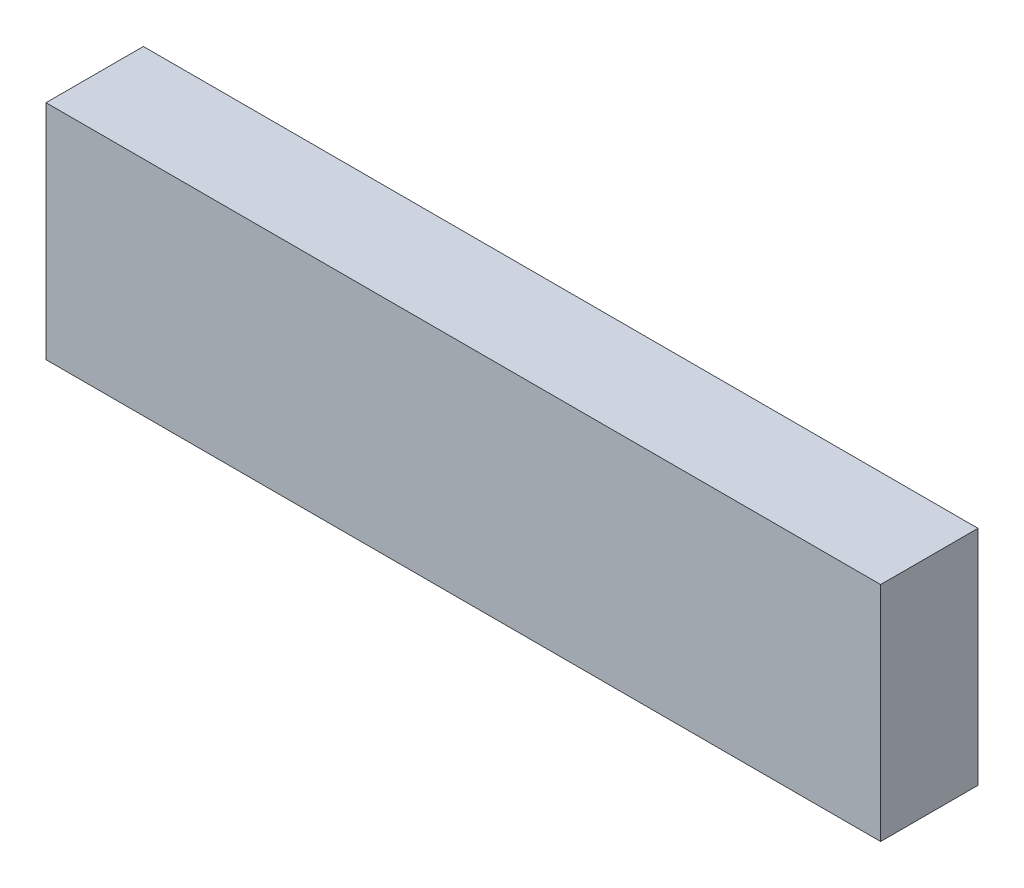
SolidWorks part; units mm, degrees
ref_plane "Front Plane" through (0, 0, 0) normal (0, 0, 1) x (1, 0, 0)
ref_plane "Top Plane" through (0, 0, 0) normal (0, 1, 0) x (1, 0, 0)
ref_plane "Right Plane" through (0, 0, 0) normal (1, 0, 0) x (0, 0, -1)
sketch "Model" plane through (0, 0, 0) normal (0, 0, 1) x (1, 0, 0)
  line L0 (-7.2181, -3.2868) -> (-7.583, -3.287)
  line L1 (-7.118, -3.4273) -> (-7.118, -3.2868)
  line L3 (-7.2181, -3.427) -> (-7.2181, -3.2868)
  line L4 (-7.118, -3.2868) -> (-6.7951, -3.2868)
  line L6 (-6.695, -3.4273) -> (-6.695, -3.2868)
  line L7 (-6.7951, -3.427) -> (-6.7951, -3.2868)
  line L9 (-6.695, -3.2868) -> (-6.3721, -3.2868)
  line L10 (-6.272, -3.4273) -> (-6.272, -3.2868)
  line L12 (-6.3721, -3.427) -> (-6.3721, -3.2868)
  line L13 (-6.272, -3.2868) -> (-5.9491, -3.2868)
  line L15 (-5.849, -3.4273) -> (-5.849, -3.2868)
  line L16 (-5.9491, -3.427) -> (-5.9491, -3.2868)
  line L18 (-5.849, -3.2868) -> (-5.5261, -3.2868)
  line L19 (-5.426, -3.4273) -> (-5.426, -3.2868)
  line L21 (-5.5261, -3.427) -> (-5.5261, -3.2868)
  line L22 (-5.426, -3.2868) -> (-5.1031, -3.2868)
  line L24 (-5.003, -3.4273) -> (-5.003, -3.2868)
  line L25 (-5.1031, -3.427) -> (-5.1031, -3.2868)
  line L27 (-5.003, -3.2868) -> (-4.6801, -3.2868)
  line L28 (-4.58, -3.4273) -> (-4.58, -3.2868)
  line L30 (-4.6801, -3.427) -> (-4.6801, -3.2868)
  line L31 (-4.58, -3.2868) -> (-4.2571, -3.2868)
  line L33 (-4.157, -3.4273) -> (-4.157, -3.2868)
  line L34 (-4.2571, -3.427) -> (-4.2571, -3.2868)
  line L36 (-4.157, -3.2868) -> (-3.8341, -3.2868)
  line L37 (-3.734, -3.4273) -> (-3.734, -3.2868)
  line L39 (-3.8341, -3.427) -> (-3.8341, -3.2868)
  line L40 (-3.734, -3.2868) -> (-3.4111, -3.2868)
  line L42 (-3.311, -3.4273) -> (-3.311, -3.2868)
  line L43 (-3.4111, -3.427) -> (-3.4111, -3.2868)
  line L45 (-3.311, -3.2868) -> (-2.9881, -3.2868)
  line L46 (-2.888, -3.4273) -> (-2.888, -3.2868)
  line L48 (-2.9881, -3.427) -> (-2.9881, -3.2868)
  line L49 (-2.888, -3.2868) -> (-2.5651, -3.2868)
  line L51 (-2.465, -3.4273) -> (-2.465, -3.2868)
  line L52 (-2.5651, -3.427) -> (-2.5651, -3.2868)
  line L54 (-2.465, -3.2868) -> (-2.1421, -3.2868)
  line L55 (-2.042, -3.4273) -> (-2.042, -3.2868)
  line L57 (-2.1421, -3.427) -> (-2.1421, -3.2868)
  line L58 (-2.042, -3.2868) -> (-1.7191, -3.2868)
  line L60 (-1.619, -3.4273) -> (-1.619, -3.2868)
  line L61 (-1.7191, -3.427) -> (-1.7191, -3.2868)
  line L63 (-1.619, -3.2868) -> (-1.2961, -3.2868)
  line L64 (-1.196, -3.4273) -> (-1.196, -3.2868)
  line L66 (-1.2961, -3.427) -> (-1.2961, -3.2868)
  line L69 (-0.773, -3.4273) -> (-0.773, -3.2868)
  line L70 (-0.8731, -3.427) -> (-0.8731, -3.2868)
  line L72 (-1.196, -3.2868) -> (-0.8731, -3.2868)
  line L73 (-0.35, -3.4273) -> (-0.35, -3.2868)
  line L75 (-0.4501, -3.427) -> (-0.4501, -3.2868)
  line L76 (-0.773, -3.2868) -> (-0.4501, -3.2868)
  line L78 (0.073, -3.4273) -> (0.073, -3.2868)
  line L79 (-0.0271, -3.427) -> (-0.0271, -3.2868)
  line L81 (-0.35, -3.2868) -> (-0.0271, -3.2868)
  line L82 (0.496, -3.4273) -> (0.496, -3.2868)
  line L84 (0.3959, -3.427) -> (0.3959, -3.2868)
  line L85 (0.073, -3.2868) -> (0.3959, -3.2868)
  line L87 (0.919, -3.4273) -> (0.919, -3.2868)
  line L88 (0.8189, -3.427) -> (0.8189, -3.2868)
  line L90 (0.496, -3.2868) -> (0.8189, -3.2868)
  line L91 (1.342, -3.4273) -> (1.342, -3.2868)
  line L93 (1.2419, -3.427) -> (1.2419, -3.2868)
  line L94 (0.919, -3.2868) -> (1.2419, -3.2868)
  line L96 (1.765, -3.4273) -> (1.765, -3.2868)
  line L97 (1.6649, -3.427) -> (1.6649, -3.2868)
  line L99 (1.342, -3.2868) -> (1.6649, -3.2868)
  line L100 (2.188, -3.4273) -> (2.188, -3.2868)
  line L102 (2.0879, -3.427) -> (2.0879, -3.2868)
  line L103 (1.765, -3.2868) -> (2.0879, -3.2868)
  line L105 (2.611, -3.4273) -> (2.611, -3.2868)
  line L106 (2.5109, -3.427) -> (2.5109, -3.2868)
  line L108 (2.188, -3.2868) -> (2.5109, -3.2868)
  line L109 (3.034, -3.4273) -> (3.034, -3.2868)
  line L111 (2.9339, -3.427) -> (2.9339, -3.2868)
  line L112 (2.611, -3.2868) -> (2.9339, -3.2868)
  line L114 (3.457, -3.4273) -> (3.457, -3.2868)
  line L115 (3.3569, -3.427) -> (3.3569, -3.2868)
  line L117 (3.034, -3.2868) -> (3.3569, -3.2868)
  line L118 (3.88, -3.4273) -> (3.88, -3.2868)
  line L120 (3.7799, -3.427) -> (3.7799, -3.2868)
  line L121 (3.457, -3.2868) -> (3.7799, -3.2868)
  line L123 (4.303, -3.4273) -> (4.303, -3.2868)
  line L124 (4.2029, -3.427) -> (4.2029, -3.2868)
  line L126 (3.88, -3.2868) -> (4.2029, -3.2868)
  line L127 (4.726, -3.4273) -> (4.726, -3.2868)
  line L129 (4.6259, -3.427) -> (4.6259, -3.2868)
  line L130 (4.303, -3.2868) -> (4.6259, -3.2868)
  line L132 (5.149, -3.4273) -> (5.149, -3.2868)
  line L133 (5.0489, -3.427) -> (5.0489, -3.2868)
  line L135 (4.726, -3.2868) -> (5.0489, -3.2868)
  line L136 (5.572, -3.4273) -> (5.572, -3.2868)
  line L138 (5.4719, -3.427) -> (5.4719, -3.2868)
  line L139 (5.149, -3.2868) -> (5.4719, -3.2868)
  line L141 (5.995, -3.4273) -> (5.995, -3.2868)
  line L142 (5.8949, -3.427) -> (5.8949, -3.2868)
  line L144 (5.572, -3.2868) -> (5.8949, -3.2868)
  line L145 (6.418, -3.4273) -> (6.418, -3.2868)
  line L147 (6.3179, -3.427) -> (6.3179, -3.2868)
  line L148 (5.995, -3.2868) -> (6.3179, -3.2868)
  line L150 (6.841, -3.4273) -> (6.841, -3.2868)
  line L151 (6.7409, -3.427) -> (6.7409, -3.2868)
  line L153 (6.418, -3.2868) -> (6.7409, -3.2868)
  line L154 (7.264, -3.4273) -> (7.264, -3.2868)
  line L156 (7.1639, -3.427) -> (7.1639, -3.2868)
  line L157 (6.841, -3.2868) -> (7.1639, -3.2868)
  line L159 (7.687, -3.4273) -> (7.687, -3.2868)
  line L160 (7.5869, -3.427) -> (7.5869, -3.2868)
  line L162 (7.264, -3.2868) -> (7.5869, -3.2868)
  line L163 (8.11, -3.4273) -> (8.11, -3.2868)
  line L165 (8.0099, -3.427) -> (8.0099, -3.2868)
  line L166 (7.687, -3.2868) -> (8.0099, -3.2868)
  line L168 (8.533, -3.4273) -> (8.533, -3.2868)
  line L169 (8.4329, -3.427) -> (8.4329, -3.2868)
  line L171 (8.11, -3.2868) -> (8.4329, -3.2868)
  line L172 (8.956, -3.4273) -> (8.956, -3.2868)
  line L174 (8.8559, -3.427) -> (8.8559, -3.2868)
  line L175 (8.533, -3.2868) -> (8.8559, -3.2868)
  line L177 (9.379, -3.4273) -> (9.379, -3.2868)
  line L178 (9.2789, -3.427) -> (9.2789, -3.2868)
  line L180 (8.956, -3.2868) -> (9.2789, -3.2868)
  line L181 (9.802, -3.4273) -> (9.802, -3.2868)
  line L183 (9.7019, -3.427) -> (9.7019, -3.2868)
  line L184 (9.379, -3.2868) -> (9.7019, -3.2868)
  line L186 (10.225, -3.4273) -> (10.225, -3.2868)
  line L187 (10.1249, -3.427) -> (10.1249, -3.2868)
  line L189 (9.802, -3.2868) -> (10.1249, -3.2868)
  line L190 (10.648, -3.4273) -> (10.648, -3.2868)
  line L192 (10.5479, -3.427) -> (10.5479, -3.2868)
  line L193 (10.225, -3.2868) -> (10.5479, -3.2868)
  line L195 (11.071, -3.4273) -> (11.071, -3.2868)
  line L196 (10.9709, -3.427) -> (10.9709, -3.2868)
  line L198 (10.648, -3.2868) -> (10.9709, -3.2868)
  line L199 (11.494, -3.4273) -> (11.494, -3.2868)
  line L201 (11.3939, -3.427) -> (11.3939, -3.2868)
  line L202 (11.071, -3.2868) -> (11.3939, -3.2868)
  line L204 (11.917, -3.4273) -> (11.917, -3.2868)
  line L205 (11.8169, -3.427) -> (11.8169, -3.2868)
  line L207 (11.494, -3.2868) -> (11.8169, -3.2868)
  line L208 (12.34, -3.4273) -> (12.34, -3.2868)
  line L210 (12.2399, -3.427) -> (12.2399, -3.2868)
  line L211 (11.917, -3.2868) -> (12.2399, -3.2868)
  line L213 (12.763, -3.4273) -> (12.763, -3.2868)
  line L214 (12.6629, -3.427) -> (12.6629, -3.2868)
  line L216 (-7.118, -4.1773) -> (-7.118, -4.0368)
  line L217 (-7.2181, -4.177) -> (-7.2181, -4.0368)
  line L219 (-7.118, -4.0368) -> (-6.7951, -4.0368)
  line L220 (-6.695, -4.1773) -> (-6.695, -4.0368)
  line L224 (-6.7951, -4.177) -> (-6.7951, -4.0368)
  line L225 (-6.695, -4.0368) -> (-6.3721, -4.0368)
  line L226 (-6.272, -4.1773) -> (-6.272, -4.0368)
  line L227 (-6.3721, -4.177) -> (-6.3721, -4.0368)
  line L228 (-6.272, -4.0368) -> (-5.9491, -4.0368)
  line L229 (-5.849, -4.1773) -> (-5.849, -4.0368)
  line L231 (-5.9491, -4.177) -> (-5.9491, -4.0368)
  line L232 (-5.849, -4.0368) -> (-5.5261, -4.0368)
  line L234 (-5.426, -4.1773) -> (-5.426, -4.0368)
  line L235 (-5.5261, -4.177) -> (-5.5261, -4.0368)
  line L237 (-5.426, -4.0368) -> (-5.1031, -4.0368)
  line L238 (-5.003, -4.1773) -> (-5.003, -4.0368)
  line L240 (-5.1031, -4.177) -> (-5.1031, -4.0368)
  line L241 (-5.003, -4.0368) -> (-4.6801, -4.0368)
  line L243 (-4.58, -4.1773) -> (-4.58, -4.0368)
  line L244 (-4.6801, -4.177) -> (-4.6801, -4.0368)
  line L246 (-4.58, -4.0368) -> (-4.2571, -4.0368)
  line L247 (-4.157, -4.1773) -> (-4.157, -4.0368)
  line L249 (-4.2571, -4.177) -> (-4.2571, -4.0368)
  line L250 (-4.157, -4.0368) -> (-3.8341, -4.0368)
  line L252 (-3.734, -4.1773) -> (-3.734, -4.0368)
  line L253 (-3.8341, -4.177) -> (-3.8341, -4.0368)
  line L255 (-3.734, -4.0368) -> (-3.4111, -4.0368)
  line L256 (-3.311, -4.1773) -> (-3.311, -4.0368)
  line L258 (-3.4111, -4.177) -> (-3.4111, -4.0368)
  line L259 (-3.311, -4.0368) -> (-2.9881, -4.0368)
  line L261 (-2.888, -4.1773) -> (-2.888, -4.0368)
  line L262 (-2.9881, -4.177) -> (-2.9881, -4.0368)
  line L264 (-2.888, -4.0368) -> (-2.5651, -4.0368)
  line L265 (-2.465, -4.1773) -> (-2.465, -4.0368)
  line L267 (-2.5651, -4.177) -> (-2.5651, -4.0368)
  line L268 (-2.465, -4.0368) -> (-2.1421, -4.0368)
  line L270 (-2.042, -4.1773) -> (-2.042, -4.0368)
  line L271 (-2.1421, -4.177) -> (-2.1421, -4.0368)
  line L273 (-2.042, -4.0368) -> (-1.7191, -4.0368)
  line L274 (-1.619, -4.1773) -> (-1.619, -4.0368)
  line L276 (-1.7191, -4.177) -> (-1.7191, -4.0368)
  line L277 (-1.619, -4.0368) -> (-1.2961, -4.0368)
  line L279 (-1.196, -4.1773) -> (-1.196, -4.0368)
  line L280 (-1.2961, -4.177) -> (-1.2961, -4.0368)
  line L282 (-0.773, -4.1773) -> (-0.773, -4.0368)
  line L283 (-0.8731, -4.177) -> (-0.8731, -4.0368)
  line L285 (-1.196, -4.0368) -> (-0.8731, -4.0368)
  line L286 (-0.35, -4.1773) -> (-0.35, -4.0368)
  line L288 (-0.4501, -4.177) -> (-0.4501, -4.0368)
  line L289 (-0.773, -4.0368) -> (-0.4501, -4.0368)
  line L291 (0.073, -4.1773) -> (0.073, -4.0368)
  line L292 (-0.0271, -4.177) -> (-0.0271, -4.0368)
  line L294 (-0.35, -4.0368) -> (-0.0271, -4.0368)
  line L295 (0.496, -4.1773) -> (0.496, -4.0368)
  line L297 (0.3959, -4.177) -> (0.3959, -4.0368)
  line L298 (0.073, -4.0368) -> (0.3959, -4.0368)
  line L300 (0.919, -4.1773) -> (0.919, -4.0368)
  line L301 (0.8189, -4.177) -> (0.8189, -4.0368)
  line L303 (0.496, -4.0368) -> (0.8189, -4.0368)
  line L304 (1.342, -4.1773) -> (1.342, -4.0368)
  line L306 (1.2419, -4.177) -> (1.2419, -4.0368)
  line L307 (0.919, -4.0368) -> (1.2419, -4.0368)
  line L309 (1.765, -4.1773) -> (1.765, -4.0368)
  line L310 (1.6649, -4.177) -> (1.6649, -4.0368)
  line L312 (1.342, -4.0368) -> (1.6649, -4.0368)
  line L313 (2.188, -4.1773) -> (2.188, -4.0368)
  line L315 (2.0879, -4.177) -> (2.0879, -4.0368)
  line L316 (1.765, -4.0368) -> (2.0879, -4.0368)
  line L318 (2.611, -4.1773) -> (2.611, -4.0368)
  line L319 (2.5109, -4.177) -> (2.5109, -4.0368)
  line L321 (2.188, -4.0368) -> (2.5109, -4.0368)
  line L322 (3.034, -4.1773) -> (3.034, -4.0368)
  line L324 (2.9339, -4.177) -> (2.9339, -4.0368)
  line L325 (2.611, -4.0368) -> (2.9339, -4.0368)
  line L327 (3.457, -4.1773) -> (3.457, -4.0368)
  line L328 (3.3569, -4.177) -> (3.3569, -4.0368)
  line L330 (3.034, -4.0368) -> (3.3569, -4.0368)
  line L331 (3.88, -4.1773) -> (3.88, -4.0368)
  line L333 (3.7799, -4.177) -> (3.7799, -4.0368)
  line L334 (3.457, -4.0368) -> (3.7799, -4.0368)
  line L336 (4.303, -4.1773) -> (4.303, -4.0368)
  line L337 (4.2029, -4.177) -> (4.2029, -4.0368)
  line L339 (3.88, -4.0368) -> (4.2029, -4.0368)
  line L340 (4.726, -4.1773) -> (4.726, -4.0368)
  line L342 (4.6259, -4.177) -> (4.6259, -4.0368)
  line L343 (4.303, -4.0368) -> (4.6259, -4.0368)
  line L345 (5.149, -4.1773) -> (5.149, -4.0368)
  line L346 (5.0489, -4.177) -> (5.0489, -4.0368)
  line L348 (4.726, -4.0368) -> (5.0489, -4.0368)
  line L349 (5.572, -4.1773) -> (5.572, -4.0368)
  line L351 (5.4719, -4.177) -> (5.4719, -4.0368)
  line L352 (5.149, -4.0368) -> (5.4719, -4.0368)
  line L354 (5.995, -4.1773) -> (5.995, -4.0368)
  line L355 (5.8949, -4.177) -> (5.8949, -4.0368)
  line L357 (5.572, -4.0368) -> (5.8949, -4.0368)
  line L358 (6.418, -4.1773) -> (6.418, -4.0368)
  line L360 (6.3179, -4.177) -> (6.3179, -4.0368)
  line L361 (5.995, -4.0368) -> (6.3179, -4.0368)
  line L363 (6.841, -4.1773) -> (6.841, -4.0368)
  line L364 (6.7409, -4.177) -> (6.7409, -4.0368)
  line L366 (6.418, -4.0368) -> (6.7409, -4.0368)
  line L367 (7.264, -4.1773) -> (7.264, -4.0368)
  line L369 (7.1639, -4.177) -> (7.1639, -4.0368)
  line L370 (6.841, -4.0368) -> (7.1639, -4.0368)
  line L372 (7.687, -4.1773) -> (7.687, -4.0368)
  line L373 (7.5869, -4.177) -> (7.5869, -4.0368)
  line L375 (7.264, -4.0368) -> (7.5869, -4.0368)
  line L376 (8.11, -4.1773) -> (8.11, -4.0368)
  line L378 (8.0099, -4.177) -> (8.0099, -4.0368)
  line L379 (7.687, -4.0368) -> (8.0099, -4.0368)
  line L381 (8.533, -4.1773) -> (8.533, -4.0368)
  line L382 (8.4329, -4.177) -> (8.4329, -4.0368)
  line L384 (8.11, -4.0368) -> (8.4329, -4.0368)
  line L385 (8.956, -4.1773) -> (8.956, -4.0368)
  line L387 (8.8559, -4.177) -> (8.8559, -4.0368)
  line L388 (8.533, -4.0368) -> (8.8559, -4.0368)
  line L390 (9.379, -4.1773) -> (9.379, -4.0368)
  line L391 (9.2789, -4.177) -> (9.2789, -4.0368)
  line L393 (8.956, -4.0368) -> (9.2789, -4.0368)
  line L394 (9.802, -4.1773) -> (9.802, -4.0368)
  line L396 (9.7019, -4.177) -> (9.7019, -4.0368)
  line L397 (9.379, -4.0368) -> (9.7019, -4.0368)
  line L399 (10.225, -4.1773) -> (10.225, -4.0368)
  line L400 (10.1249, -4.177) -> (10.1249, -4.0368)
  line L402 (9.802, -4.0368) -> (10.1249, -4.0368)
  line L403 (10.648, -4.1773) -> (10.648, -4.0368)
  line L405 (10.5479, -4.177) -> (10.5479, -4.0368)
  line L406 (10.225, -4.0368) -> (10.5479, -4.0368)
  line L408 (11.071, -4.1773) -> (11.071, -4.0368)
  line L409 (10.9709, -4.177) -> (10.9709, -4.0368)
  line L411 (10.648, -4.0368) -> (10.9709, -4.0368)
  line L412 (11.494, -4.1773) -> (11.494, -4.0368)
  line L414 (11.3939, -4.177) -> (11.3939, -4.0368)
  line L415 (11.071, -4.0368) -> (11.3939, -4.0368)
  line L417 (11.917, -4.1773) -> (11.917, -4.0368)
  line L418 (11.8169, -4.177) -> (11.8169, -4.0368)
  line L420 (11.494, -4.0368) -> (11.8169, -4.0368)
  line L421 (12.34, -4.1773) -> (12.34, -4.0368)
  line L423 (12.2399, -4.177) -> (12.2399, -4.0368)
  line L424 (11.917, -4.0368) -> (12.2399, -4.0368)
  line L426 (12.763, -4.1773) -> (12.763, -4.0368)
  line L427 (12.6629, -4.177) -> (12.6629, -4.0368)
  line L429 (12.34, -4.0368) -> (12.6629, -4.0368)
  line L430 (12.763, -4.0368) -> (13.18, -4.0368)
  line L432 (13.28, -3.1775) -> (13.28, -3.5525)
  line L433 (12.34, -3.2868) -> (12.6629, -3.2868)
  line L438 (13.18, -3.1775) -> (13.28, -3.1775)
  line L439 (-7.2181, -4.0368) -> (-7.583, -4.037)
  line L441 (13.18, -4.0368) -> (13.28, -4.0368)
  line L442 (13.28, -3.6525) -> (13.28, -4.0368)
  line L444 (13.18, -3.9275) -> (13.18, -3.6525)
  line L445 (13.18, -3.5525) -> (13.18, -3.6525)
  line L447 (13.18, -3.5525) -> (13.18, -3.2868)
  line L448 (13.48, -3.6525) -> (13.48, -4.3075)
  line L451 (13.58, -3.5525) -> (13.58, -4.3075)
  line L453 (13.58, -4.4075) -> (13.58, -5.1525)
  line L454 (13.78, -4.4075) -> (13.78, -7.3075)
  line L456 (13.88, -4.3075) -> (13.88, -5.8075)
  line L457 (13.88, -5.9075) -> (13.88, -7.4075)
  line L459 (-7.683, -4.037) -> (-7.683, -3.662)
  line L460 (-7.683, -3.187) -> (-7.683, -3.562)
  line L462 (-7.583, -3.287) -> (-7.583, -3.937)
  line L463 (-7.883, -3.662) -> (-7.883, -5.062)
  line L465 (-7.983, -3.562) -> (-7.983, -4.317)
  line L466 (-7.983, -4.417) -> (-7.983, -5.162)
  line L468 (-7.683, -4.037) -> (-7.583, -4.037)
  line L469 (-7.2181, -4.7868) -> (-7.583, -4.787)
  line L471 (-7.118, -4.9273) -> (-7.118, -4.7868)
  line L472 (-7.2181, -4.927) -> (-7.2181, -4.7868)
  line L474 (-7.118, -4.7868) -> (-6.7951, -4.7868)
  line L475 (-6.695, -4.9273) -> (-6.695, -4.7868)
  line L477 (-6.7951, -4.927) -> (-6.7951, -4.7868)
  line L478 (-6.695, -4.7868) -> (-6.3721, -4.7868)
  line L480 (-6.272, -4.9273) -> (-6.272, -4.7868)
  line L481 (-6.3721, -4.927) -> (-6.3721, -4.7868)
  line L483 (-6.272, -4.7868) -> (-5.9491, -4.7868)
  line L484 (-5.849, -4.9273) -> (-5.849, -4.7868)
  line L486 (-5.9491, -4.927) -> (-5.9491, -4.7868)
  line L487 (-5.849, -4.7868) -> (-5.5261, -4.7868)
  line L489 (-5.426, -4.9273) -> (-5.426, -4.7868)
  line L490 (-5.5261, -4.927) -> (-5.5261, -4.7868)
  line L492 (-5.426, -4.7868) -> (-5.1031, -4.7868)
  line L493 (-5.003, -4.9273) -> (-5.003, -4.7868)
  line L495 (-5.1031, -4.927) -> (-5.1031, -4.7868)
  line L496 (-5.003, -4.7868) -> (-4.6801, -4.7868)
  line L498 (-4.58, -4.9273) -> (-4.58, -4.7868)
  line L499 (-4.6801, -4.927) -> (-4.6801, -4.7868)
  line L501 (-4.58, -4.7868) -> (-4.2571, -4.7868)
  line L502 (-4.157, -4.9273) -> (-4.157, -4.7868)
  line L504 (-4.2571, -4.927) -> (-4.2571, -4.7868)
  line L505 (-4.157, -4.7868) -> (-3.8341, -4.7868)
  line L507 (-3.734, -4.9273) -> (-3.734, -4.7868)
  line L508 (-3.8341, -4.927) -> (-3.8341, -4.7868)
  line L510 (-3.734, -4.7868) -> (-3.4111, -4.7868)
  line L514 (-3.311, -4.9273) -> (-3.311, -4.7868)
  line L516 (-3.4111, -4.927) -> (-3.4111, -4.7868)
  line L517 (-3.311, -4.7868) -> (-2.9881, -4.7868)
  line L519 (-2.888, -4.9273) -> (-2.888, -4.7868)
  line L520 (-2.9881, -4.927) -> (-2.9881, -4.7868)
  line L522 (-2.888, -4.7868) -> (-2.5651, -4.7868)
  line L523 (-2.465, -4.9273) -> (-2.465, -4.7868)
  line L525 (-2.5651, -4.927) -> (-2.5651, -4.7868)
  line L526 (-2.465, -4.7868) -> (-2.1421, -4.7868)
  line L528 (-2.042, -4.9273) -> (-2.042, -4.7868)
  line L529 (-2.1421, -4.927) -> (-2.1421, -4.7868)
  line L531 (-2.042, -4.7868) -> (-1.7191, -4.7868)
  line L532 (-1.619, -4.9273) -> (-1.619, -4.7868)
  line L534 (-1.7191, -4.927) -> (-1.7191, -4.7868)
  line L535 (-1.619, -4.7868) -> (-1.2961, -4.7868)
  line L537 (-1.196, -4.9273) -> (-1.196, -4.7868)
  line L538 (-1.2961, -4.927) -> (-1.2961, -4.7868)
  line L540 (-0.773, -4.9273) -> (-0.773, -4.7868)
  line L541 (-0.8731, -4.927) -> (-0.8731, -4.7868)
  line L543 (-1.196, -4.7868) -> (-0.8731, -4.7868)
  line L544 (-0.35, -4.9273) -> (-0.35, -4.7868)
  line L546 (-0.4501, -4.927) -> (-0.4501, -4.7868)
  line L547 (-0.773, -4.7868) -> (-0.4501, -4.7868)
  line L549 (0.073, -4.9273) -> (0.073, -4.7868)
  line L550 (-0.0271, -4.927) -> (-0.0271, -4.7868)
  line L552 (-0.35, -4.7868) -> (-0.0271, -4.7868)
  line L553 (0.496, -4.9273) -> (0.496, -4.7868)
  line L555 (0.3959, -4.927) -> (0.3959, -4.7868)
  line L556 (0.073, -4.7868) -> (0.3959, -4.7868)
  line L558 (0.919, -4.9273) -> (0.919, -4.7868)
  line L559 (0.8189, -4.927) -> (0.8189, -4.7868)
  line L561 (0.496, -4.7868) -> (0.8189, -4.7868)
  line L562 (1.342, -4.9273) -> (1.342, -4.7868)
  line L564 (1.2419, -4.927) -> (1.2419, -4.7868)
  line L565 (0.919, -4.7868) -> (1.2419, -4.7868)
  line L567 (1.765, -4.9273) -> (1.765, -4.7868)
  line L568 (1.6649, -4.927) -> (1.6649, -4.7868)
  line L570 (1.342, -4.7868) -> (1.6649, -4.7868)
  line L571 (2.188, -4.9273) -> (2.188, -4.7868)
  line L573 (2.0879, -4.927) -> (2.0879, -4.7868)
  line L574 (1.765, -4.7868) -> (2.0879, -4.7868)
  line L576 (2.611, -4.9273) -> (2.611, -4.7868)
  line L577 (2.5109, -4.927) -> (2.5109, -4.7868)
  line L579 (2.188, -4.7868) -> (2.5109, -4.7868)
  line L580 (3.034, -4.9273) -> (3.034, -4.7868)
  line L582 (2.9339, -4.927) -> (2.9339, -4.7868)
  line L583 (2.611, -4.7868) -> (2.9339, -4.7868)
  line L585 (3.457, -4.9273) -> (3.457, -4.7868)
  line L586 (3.3569, -4.927) -> (3.3569, -4.7868)
  line L588 (3.034, -4.7868) -> (3.3569, -4.7868)
  line L589 (3.88, -4.9273) -> (3.88, -4.7868)
  line L591 (3.7799, -4.927) -> (3.7799, -4.7868)
  line L592 (3.457, -4.7868) -> (3.7799, -4.7868)
  line L594 (4.303, -4.9273) -> (4.303, -4.7868)
  line L595 (4.2029, -4.927) -> (4.2029, -4.7868)
  line L597 (3.88, -4.7868) -> (4.2029, -4.7868)
  line L598 (4.726, -4.9273) -> (4.726, -4.7868)
  line L600 (4.6259, -4.927) -> (4.6259, -4.7868)
  line L601 (4.303, -4.7868) -> (4.6259, -4.7868)
  line L603 (5.149, -4.9273) -> (5.149, -4.7868)
  line L604 (5.0489, -4.927) -> (5.0489, -4.7868)
  line L606 (4.726, -4.7868) -> (5.0489, -4.7868)
  line L607 (5.572, -4.9273) -> (5.572, -4.7868)
  line L609 (5.4719, -4.927) -> (5.4719, -4.7868)
  line L610 (5.149, -4.7868) -> (5.4719, -4.7868)
  line L612 (5.995, -4.9273) -> (5.995, -4.7868)
  line L613 (5.8949, -4.927) -> (5.8949, -4.7868)
  line L615 (5.572, -4.7868) -> (5.8949, -4.7868)
  line L616 (6.418, -4.9273) -> (6.418, -4.7868)
  line L618 (6.3179, -4.927) -> (6.3179, -4.7868)
  line L619 (5.995, -4.7868) -> (6.3179, -4.7868)
  line L621 (6.841, -4.9273) -> (6.841, -4.7868)
  line L622 (6.7409, -4.927) -> (6.7409, -4.7868)
  line L624 (6.418, -4.7868) -> (6.7409, -4.7868)
  line L625 (7.264, -4.9273) -> (7.264, -4.7868)
  line L627 (7.1639, -4.927) -> (7.1639, -4.7868)
  line L628 (6.841, -4.7868) -> (7.1639, -4.7868)
  line L630 (7.687, -4.9273) -> (7.687, -4.7868)
  line L631 (7.5869, -4.927) -> (7.5869, -4.7868)
  line L633 (7.264, -4.7868) -> (7.5869, -4.7868)
  line L634 (8.11, -4.9273) -> (8.11, -4.7868)
  line L636 (8.0099, -4.927) -> (8.0099, -4.7868)
  line L637 (7.687, -4.7868) -> (8.0099, -4.7868)
  line L639 (8.533, -4.9273) -> (8.533, -4.7868)
  line L640 (8.4329, -4.927) -> (8.4329, -4.7868)
  line L642 (8.11, -4.7868) -> (8.4329, -4.7868)
  line L643 (8.956, -4.9273) -> (8.956, -4.7868)
  line L645 (8.8559, -4.927) -> (8.8559, -4.7868)
  line L646 (8.533, -4.7868) -> (8.8559, -4.7868)
  line L650 (9.379, -4.9273) -> (9.379, -4.7868)
  line L651 (9.2789, -4.927) -> (9.2789, -4.7868)
  line L652 (8.956, -4.7868) -> (9.2789, -4.7868)
  line L653 (9.802, -4.9273) -> (9.802, -4.7868)
  line L654 (9.7019, -4.927) -> (9.7019, -4.7868)
  line L655 (9.379, -4.7868) -> (9.7019, -4.7868)
  line L657 (10.225, -4.9273) -> (10.225, -4.7868)
  line L658 (10.1249, -4.927) -> (10.1249, -4.7868)
  line L660 (9.802, -4.7868) -> (10.1249, -4.7868)
  line L661 (10.648, -4.9273) -> (10.648, -4.7868)
  line L663 (10.5479, -4.927) -> (10.5479, -4.7868)
  line L664 (10.225, -4.7868) -> (10.5479, -4.7868)
  line L666 (11.071, -4.9273) -> (11.071, -4.7868)
  line L667 (10.9709, -4.927) -> (10.9709, -4.7868)
  line L669 (10.648, -4.7868) -> (10.9709, -4.7868)
  line L670 (11.494, -4.9273) -> (11.494, -4.7868)
  line L672 (11.3939, -4.927) -> (11.3939, -4.7868)
  line L673 (11.071, -4.7868) -> (11.3939, -4.7868)
  line L675 (11.917, -4.9273) -> (11.917, -4.7868)
  line L676 (11.8169, -4.927) -> (11.8169, -4.7868)
  line L678 (11.494, -4.7868) -> (11.8169, -4.7868)
  line L679 (12.34, -4.9273) -> (12.34, -4.7868)
  line L681 (12.2399, -4.927) -> (12.2399, -4.7868)
  line L682 (11.917, -4.7868) -> (12.2399, -4.7868)
  line L684 (12.763, -4.9273) -> (12.763, -4.7868)
  line L685 (12.6629, -4.927) -> (12.6629, -4.7868)
  line L687 (-7.118, -5.6773) -> (-7.118, -5.5368)
  line L688 (-7.2181, -5.677) -> (-7.2181, -5.5368)
  line L690 (-7.118, -5.5368) -> (-6.7951, -5.5368)
  line L691 (-6.695, -5.6773) -> (-6.695, -5.5368)
  line L693 (-6.7951, -5.677) -> (-6.7951, -5.5368)
  line L694 (-6.695, -5.5368) -> (-6.3721, -5.5368)
  line L696 (-6.272, -5.6773) -> (-6.272, -5.5368)
  line L697 (-6.3721, -5.677) -> (-6.3721, -5.5368)
  line L699 (-6.272, -5.5368) -> (-5.9491, -5.5368)
  line L700 (-5.849, -5.6773) -> (-5.849, -5.5368)
  line L702 (-5.9491, -5.677) -> (-5.9491, -5.5368)
  line L703 (-5.849, -5.5368) -> (-5.5261, -5.5368)
  line L705 (-5.426, -5.6773) -> (-5.426, -5.5368)
  line L706 (-5.5261, -5.677) -> (-5.5261, -5.5368)
  line L708 (-5.426, -5.5368) -> (-5.1031, -5.5368)
  line L709 (-5.003, -5.6773) -> (-5.003, -5.5368)
  line L711 (-5.1031, -5.677) -> (-5.1031, -5.5368)
  line L712 (-5.003, -5.5368) -> (-4.6801, -5.5368)
  line L714 (-4.58, -5.6773) -> (-4.58, -5.5368)
  line L715 (-4.6801, -5.677) -> (-4.6801, -5.5368)
  line L717 (-4.58, -5.5368) -> (-4.2571, -5.5368)
  line L718 (-4.157, -5.6773) -> (-4.157, -5.5368)
  line L720 (-4.2571, -5.677) -> (-4.2571, -5.5368)
  line L721 (-4.157, -5.5368) -> (-3.8341, -5.5368)
  line L723 (-3.734, -5.6773) -> (-3.734, -5.5368)
  line L724 (-3.8341, -5.677) -> (-3.8341, -5.5368)
  line L726 (-3.734, -5.5368) -> (-3.4111, -5.5368)
  line L727 (-3.311, -5.6773) -> (-3.311, -5.5368)
  line L729 (-3.4111, -5.677) -> (-3.4111, -5.5368)
  line L730 (-3.311, -5.5368) -> (-2.9881, -5.5368)
  line L732 (-2.888, -5.6773) -> (-2.888, -5.5368)
  line L733 (-2.9881, -5.677) -> (-2.9881, -5.5368)
  line L735 (-2.888, -5.5368) -> (-2.5651, -5.5368)
  line L736 (-2.465, -5.6773) -> (-2.465, -5.5368)
  line L738 (-2.5651, -5.677) -> (-2.5651, -5.5368)
  line L739 (-2.465, -5.5368) -> (-2.1421, -5.5368)
  line L741 (-2.042, -5.6773) -> (-2.042, -5.5368)
  line L742 (-2.1421, -5.677) -> (-2.1421, -5.5368)
  line L744 (-2.042, -5.5368) -> (-1.7191, -5.5368)
  line L745 (-1.619, -5.6773) -> (-1.619, -5.5368)
  line L747 (-1.7191, -5.677) -> (-1.7191, -5.5368)
  line L748 (-1.619, -5.5368) -> (-1.2961, -5.5368)
  line L750 (-1.196, -5.6773) -> (-1.196, -5.5368)
  line L751 (-1.2961, -5.677) -> (-1.2961, -5.5368)
  line L753 (-0.773, -5.6773) -> (-0.773, -5.5368)
  line L754 (-0.8731, -5.677) -> (-0.8731, -5.5368)
  line L756 (-1.196, -5.5368) -> (-0.8731, -5.5368)
  line L757 (-0.35, -5.6773) -> (-0.35, -5.5368)
  line L759 (-0.4501, -5.677) -> (-0.4501, -5.5368)
  line L760 (-0.773, -5.5368) -> (-0.4501, -5.5368)
  line L762 (0.073, -5.6773) -> (0.073, -5.5368)
  line L763 (-0.0271, -5.677) -> (-0.0271, -5.5368)
  line L765 (-0.35, -5.5368) -> (-0.0271, -5.5368)
  line L766 (0.496, -5.6773) -> (0.496, -5.5368)
  line L768 (0.3959, -5.677) -> (0.3959, -5.5368)
  line L769 (0.073, -5.5368) -> (0.3959, -5.5368)
  line L771 (0.919, -5.6773) -> (0.919, -5.5368)
  line L772 (0.8189, -5.677) -> (0.8189, -5.5368)
  line L774 (0.496, -5.5368) -> (0.8189, -5.5368)
  line L775 (1.342, -5.6773) -> (1.342, -5.5368)
  line L777 (1.2419, -5.677) -> (1.2419, -5.5368)
  line L778 (0.919, -5.5368) -> (1.2419, -5.5368)
  line L780 (1.765, -5.6773) -> (1.765, -5.5368)
  line L781 (1.6649, -5.677) -> (1.6649, -5.5368)
  line L783 (1.342, -5.5368) -> (1.6649, -5.5368)
  line L784 (2.188, -5.6773) -> (2.188, -5.5368)
  line L786 (2.0879, -5.677) -> (2.0879, -5.5368)
  line L787 (1.765, -5.5368) -> (2.0879, -5.5368)
  line L789 (2.611, -5.6773) -> (2.611, -5.5368)
  line L790 (2.5109, -5.677) -> (2.5109, -5.5368)
  line L792 (2.188, -5.5368) -> (2.5109, -5.5368)
  line L793 (3.034, -5.6773) -> (3.034, -5.5368)
  line L795 (2.9339, -5.677) -> (2.9339, -5.5368)
  line L796 (2.611, -5.5368) -> (2.9339, -5.5368)
  line L798 (3.457, -5.6773) -> (3.457, -5.5368)
  line L799 (3.3569, -5.677) -> (3.3569, -5.5368)
  line L801 (3.034, -5.5368) -> (3.3569, -5.5368)
  line L802 (3.88, -5.6773) -> (3.88, -5.5368)
  line L804 (3.7799, -5.677) -> (3.7799, -5.5368)
  line L805 (3.457, -5.5368) -> (3.7799, -5.5368)
  line L807 (4.303, -5.6773) -> (4.303, -5.5368)
  line L808 (4.2029, -5.677) -> (4.2029, -5.5368)
  line L810 (3.88, -5.5368) -> (4.2029, -5.5368)
  line L811 (4.726, -5.6773) -> (4.726, -5.5368)
  line L813 (4.6259, -5.677) -> (4.6259, -5.5368)
  line L814 (4.303, -5.5368) -> (4.6259, -5.5368)
  line L816 (5.149, -5.6773) -> (5.149, -5.5368)
  line L817 (5.0489, -5.677) -> (5.0489, -5.5368)
  line L819 (4.726, -5.5368) -> (5.0489, -5.5368)
  line L820 (5.572, -5.6773) -> (5.572, -5.5368)
  line L822 (5.4719, -5.677) -> (5.4719, -5.5368)
  line L823 (5.149, -5.5368) -> (5.4719, -5.5368)
  line L825 (5.995, -5.6773) -> (5.995, -5.5368)
  line L826 (5.8949, -5.677) -> (5.8949, -5.5368)
  line L828 (5.572, -5.5368) -> (5.8949, -5.5368)
  line L829 (6.418, -5.6773) -> (6.418, -5.5368)
  line L831 (6.3179, -5.677) -> (6.3179, -5.5368)
  line L832 (5.995, -5.5368) -> (6.3179, -5.5368)
  line L834 (6.841, -5.6773) -> (6.841, -5.5368)
  line L835 (6.7409, -5.677) -> (6.7409, -5.5368)
  line L837 (6.418, -5.5368) -> (6.7409, -5.5368)
  line L838 (7.264, -5.6773) -> (7.264, -5.5368)
  line L840 (7.1639, -5.677) -> (7.1639, -5.5368)
  line L841 (6.841, -5.5368) -> (7.1639, -5.5368)
  line L843 (7.687, -5.6773) -> (7.687, -5.5368)
  line L844 (7.5869, -5.677) -> (7.5869, -5.5368)
  line L846 (7.264, -5.5368) -> (7.5869, -5.5368)
  line L847 (8.11, -5.6773) -> (8.11, -5.5368)
  line L849 (8.0099, -5.677) -> (8.0099, -5.5368)
  line L850 (7.687, -5.5368) -> (8.0099, -5.5368)
  line L852 (8.533, -5.6773) -> (8.533, -5.5368)
  line L853 (8.4329, -5.677) -> (8.4329, -5.5368)
  line L855 (8.11, -5.5368) -> (8.4329, -5.5368)
  line L856 (8.956, -5.6773) -> (8.956, -5.5368)
  line L858 (8.8559, -5.677) -> (8.8559, -5.5368)
  line L859 (8.533, -5.5368) -> (8.8559, -5.5368)
  line L861 (9.379, -5.6773) -> (9.379, -5.5368)
  line L862 (9.2789, -5.677) -> (9.2789, -5.5368)
  line L864 (8.956, -5.5368) -> (9.2789, -5.5368)
  line L865 (9.802, -5.6773) -> (9.802, -5.5368)
  line L867 (9.7019, -5.677) -> (9.7019, -5.5368)
  line L868 (9.379, -5.5368) -> (9.7019, -5.5368)
  line L870 (10.225, -5.6773) -> (10.225, -5.5368)
  line L871 (10.1249, -5.677) -> (10.1249, -5.5368)
  line L873 (9.802, -5.5368) -> (10.1249, -5.5368)
  line L874 (10.648, -5.6773) -> (10.648, -5.5368)
  line L876 (10.5479, -5.677) -> (10.5479, -5.5368)
  line L877 (10.225, -5.5368) -> (10.5479, -5.5368)
  line L879 (11.071, -5.6773) -> (11.071, -5.5368)
  line L880 (10.9709, -5.677) -> (10.9709, -5.5368)
  line L882 (10.648, -5.5368) -> (10.9709, -5.5368)
  line L883 (11.494, -5.6773) -> (11.494, -5.5368)
  line L885 (11.3939, -5.677) -> (11.3939, -5.5368)
  line L886 (11.071, -5.5368) -> (11.3939, -5.5368)
  line L888 (11.917, -5.6773) -> (11.917, -5.5368)
  line L889 (11.8169, -5.677) -> (11.8169, -5.5368)
  line L891 (11.494, -5.5368) -> (11.8169, -5.5368)
  line L892 (12.34, -5.6773) -> (12.34, -5.5368)
  line L894 (12.2399, -5.677) -> (12.2399, -5.5368)
  line L895 (11.917, -5.5368) -> (12.2399, -5.5368)
  line L897 (12.763, -5.6773) -> (12.763, -5.5368)
  line L898 (12.6629, -5.677) -> (12.6629, -5.5368)
  line L900 (12.34, -5.5368) -> (12.6629, -5.5368)
  line L901 (12.763, -5.5368) -> (13.18, -5.5368)
  line L903 (13.28, -4.6775) -> (13.28, -5.0525)
  line L904 (12.34, -4.7868) -> (12.6629, -4.7868)
  line L906 (13.18, -4.6775) -> (13.28, -4.6775)
  line L907 (-7.2181, -5.5368) -> (-7.583, -5.537)
  line L909 (13.18, -5.5368) -> (13.28, -5.5368)
  line L910 (13.28, -5.1525) -> (13.28, -5.5368)
  line L912 (13.18, -5.4275) -> (13.18, -5.1525)
  line L913 (13.18, -5.0525) -> (13.18, -5.1525)
  line L915 (13.18, -5.0525) -> (13.18, -4.7868)
  line L916 (-7.683, -5.537) -> (-7.683, -5.162)
  line L918 (-7.683, -4.687) -> (-7.683, -5.062)
  line L919 (-7.583, -4.787) -> (-7.583, -5.437)
  line L921 (-7.683, -5.537) -> (-7.583, -5.537)
  line L922 (12.763, -4.7868) -> (13.18, -4.7868)
  line L924 (-7.583, -4.687) -> (-7.683, -4.687)
  line L925 (13.18, -4.6775) -> (-7.583, -4.687)
  line L927 (13.18, -5.4275) -> (-7.583, -5.437)
  line L928 (-7.683, -5.062) -> (-7.883, -5.062)
  line L930 (-7.883, -5.162) -> (-7.683, -5.162)
  line L931 (13.48, -5.0525) -> (13.28, -5.0525)
  line L933 (13.28, -5.1525) -> (13.48, -5.1525)
  line L934 (-7.883, -5.162) -> (-7.983, -5.162)
  line L936 (13.48, -5.1525) -> (13.58, -5.1525)
  line L937 (13.48, -5.0525) -> (13.48, -4.3075)
  line L939 (-7.2181, -6.2868) -> (-7.583, -6.287)
  line L940 (-7.118, -6.4273) -> (-7.118, -6.2868)
  line L942 (-7.2181, -6.427) -> (-7.2181, -6.2868)
  line L943 (-7.118, -6.2868) -> (-6.7951, -6.2868)
  line L945 (-6.695, -6.4273) -> (-6.695, -6.2868)
  line L946 (-6.7951, -6.427) -> (-6.7951, -6.2868)
  line L948 (-6.695, -6.2868) -> (-6.3721, -6.2868)
  line L949 (-6.272, -6.4273) -> (-6.272, -6.2868)
  line L951 (-6.3721, -6.427) -> (-6.3721, -6.2868)
  line L952 (-6.272, -6.2868) -> (-5.9491, -6.2868)
  line L954 (-5.849, -6.4273) -> (-5.849, -6.2868)
  line L955 (-5.9491, -6.427) -> (-5.9491, -6.2868)
  line L957 (-5.849, -6.2868) -> (-5.5261, -6.2868)
  line L958 (-5.426, -6.4273) -> (-5.426, -6.2868)
  line L960 (-5.5261, -6.427) -> (-5.5261, -6.2868)
  line L961 (-5.426, -6.2868) -> (-5.1031, -6.2868)
  line L963 (-5.003, -6.4273) -> (-5.003, -6.2868)
  line L964 (-5.1031, -6.427) -> (-5.1031, -6.2868)
  line L966 (-5.003, -6.2868) -> (-4.6801, -6.2868)
  line L967 (-4.58, -6.4273) -> (-4.58, -6.2868)
  line L969 (-4.6801, -6.427) -> (-4.6801, -6.2868)
  line L970 (-4.58, -6.2868) -> (-4.2571, -6.2868)
  line L972 (-4.157, -6.4273) -> (-4.157, -6.2868)
  line L973 (-4.2571, -6.427) -> (-4.2571, -6.2868)
  line L975 (-4.157, -6.2868) -> (-3.8341, -6.2868)
  line L976 (-3.734, -6.4273) -> (-3.734, -6.2868)
  line L978 (-3.8341, -6.427) -> (-3.8341, -6.2868)
  line L979 (-3.734, -6.2868) -> (-3.4111, -6.2868)
  line L981 (-3.311, -6.4273) -> (-3.311, -6.2868)
  line L982 (-3.4111, -6.427) -> (-3.4111, -6.2868)
  line L984 (-3.311, -6.2868) -> (-2.9881, -6.2868)
  line L985 (-2.888, -6.4273) -> (-2.888, -6.2868)
  line L987 (-2.9881, -6.427) -> (-2.9881, -6.2868)
  line L988 (-2.888, -6.2868) -> (-2.5651, -6.2868)
  line L990 (-2.465, -6.4273) -> (-2.465, -6.2868)
  line L991 (-2.5651, -6.427) -> (-2.5651, -6.2868)
  line L993 (-2.465, -6.2868) -> (-2.1421, -6.2868)
  line L994 (-2.042, -6.4273) -> (-2.042, -6.2868)
  line L996 (-2.1421, -6.427) -> (-2.1421, -6.2868)
  line L997 (-2.042, -6.2868) -> (-1.7191, -6.2868)
  line L999 (-1.619, -6.4273) -> (-1.619, -6.2868)
  line L1000 (-1.7191, -6.427) -> (-1.7191, -6.2868)
  line L1002 (-1.619, -6.2868) -> (-1.2961, -6.2868)
  line L1003 (-1.196, -6.4273) -> (-1.196, -6.2868)
  line L1005 (-1.2961, -6.427) -> (-1.2961, -6.2868)
  line L1006 (-0.773, -6.4273) -> (-0.773, -6.2868)
  line L1008 (-0.8731, -6.427) -> (-0.8731, -6.2868)
  line L1009 (-1.196, -6.2868) -> (-0.8731, -6.2868)
  line L1011 (-0.35, -6.4273) -> (-0.35, -6.2868)
  line L1012 (-0.4501, -6.427) -> (-0.4501, -6.2868)
  line L1014 (-0.773, -6.2868) -> (-0.4501, -6.2868)
  line L1015 (0.073, -6.4273) -> (0.073, -6.2868)
  line L1017 (-0.0271, -6.427) -> (-0.0271, -6.2868)
  line L1018 (-0.35, -6.2868) -> (-0.0271, -6.2868)
  line L1020 (0.496, -6.4273) -> (0.496, -6.2868)
  line L1021 (0.3959, -6.427) -> (0.3959, -6.2868)
  line L1023 (0.073, -6.2868) -> (0.3959, -6.2868)
  line L1024 (0.919, -6.4273) -> (0.919, -6.2868)
  line L1026 (0.8189, -6.427) -> (0.8189, -6.2868)
  line L1027 (0.496, -6.2868) -> (0.8189, -6.2868)
  line L1029 (1.342, -6.4273) -> (1.342, -6.2868)
  line L1030 (1.2419, -6.427) -> (1.2419, -6.2868)
  line L1032 (0.919, -6.2868) -> (1.2419, -6.2868)
  line L1033 (1.765, -6.4273) -> (1.765, -6.2868)
  line L1035 (1.6649, -6.427) -> (1.6649, -6.2868)
  line L1036 (1.342, -6.2868) -> (1.6649, -6.2868)
  line L1038 (2.188, -6.4273) -> (2.188, -6.2868)
  line L1039 (2.0879, -6.427) -> (2.0879, -6.2868)
  line L1041 (1.765, -6.2868) -> (2.0879, -6.2868)
  line L1042 (2.611, -6.4273) -> (2.611, -6.2868)
  line L1044 (2.5109, -6.427) -> (2.5109, -6.2868)
  line L1045 (2.188, -6.2868) -> (2.5109, -6.2868)
  line L1047 (3.034, -6.4273) -> (3.034, -6.2868)
  line L1048 (2.9339, -6.427) -> (2.9339, -6.2868)
  line L1050 (2.611, -6.2868) -> (2.9339, -6.2868)
  line L1051 (3.457, -6.4273) -> (3.457, -6.2868)
  line L1053 (3.3569, -6.427) -> (3.3569, -6.2868)
  line L1054 (3.034, -6.2868) -> (3.3569, -6.2868)
  line L1056 (3.88, -6.4273) -> (3.88, -6.2868)
  line L1057 (3.7799, -6.427) -> (3.7799, -6.2868)
  line L1059 (3.457, -6.2868) -> (3.7799, -6.2868)
  line L1060 (4.303, -6.4273) -> (4.303, -6.2868)
  line L1062 (4.2029, -6.427) -> (4.2029, -6.2868)
  line L1063 (3.88, -6.2868) -> (4.2029, -6.2868)
  line L1065 (4.726, -6.4273) -> (4.726, -6.2868)
  line L1066 (4.6259, -6.427) -> (4.6259, -6.2868)
  line L1068 (4.303, -6.2868) -> (4.6259, -6.2868)
  line L1069 (5.149, -6.4273) -> (5.149, -6.2868)
  line L1071 (5.0489, -6.427) -> (5.0489, -6.2868)
  line L1072 (4.726, -6.2868) -> (5.0489, -6.2868)
  line L1074 (5.572, -6.4273) -> (5.572, -6.2868)
  line L1075 (5.4719, -6.427) -> (5.4719, -6.2868)
  line L1077 (5.149, -6.2868) -> (5.4719, -6.2868)
  line L1078 (5.995, -6.4273) -> (5.995, -6.2868)
  line L1080 (5.8949, -6.427) -> (5.8949, -6.2868)
  line L1081 (5.572, -6.2868) -> (5.8949, -6.2868)
  line L1083 (6.418, -6.4273) -> (6.418, -6.2868)
  line L1084 (6.3179, -6.427) -> (6.3179, -6.2868)
  line L1086 (5.995, -6.2868) -> (6.3179, -6.2868)
  line L1087 (6.841, -6.4273) -> (6.841, -6.2868)
  line L1089 (6.7409, -6.427) -> (6.7409, -6.2868)
  line L1090 (6.418, -6.2868) -> (6.7409, -6.2868)
  line L1092 (7.264, -6.4273) -> (7.264, -6.2868)
  line L1093 (7.1639, -6.427) -> (7.1639, -6.2868)
  line L1095 (6.841, -6.2868) -> (7.1639, -6.2868)
  line L1096 (7.687, -6.4273) -> (7.687, -6.2868)
  line L1098 (7.5869, -6.427) -> (7.5869, -6.2868)
  line L1099 (7.264, -6.2868) -> (7.5869, -6.2868)
  line L1101 (8.11, -6.4273) -> (8.11, -6.2868)
  line L1102 (8.0099, -6.427) -> (8.0099, -6.2868)
  line L1104 (7.687, -6.2868) -> (8.0099, -6.2868)
  line L1105 (8.533, -6.4273) -> (8.533, -6.2868)
  line L1107 (8.4329, -6.427) -> (8.4329, -6.2868)
  line L1108 (8.11, -6.2868) -> (8.4329, -6.2868)
  line L1110 (8.956, -6.4273) -> (8.956, -6.2868)
  line L1111 (8.8559, -6.427) -> (8.8559, -6.2868)
  line L1113 (8.533, -6.2868) -> (8.8559, -6.2868)
  line L1114 (9.379, -6.4273) -> (9.379, -6.2868)
  line L1116 (9.2789, -6.427) -> (9.2789, -6.2868)
  line L1117 (8.956, -6.2868) -> (9.2789, -6.2868)
  line L1119 (9.802, -6.4273) -> (9.802, -6.2868)
  line L1120 (9.7019, -6.427) -> (9.7019, -6.2868)
  line L1122 (9.379, -6.2868) -> (9.7019, -6.2868)
  line L1123 (10.225, -6.4273) -> (10.225, -6.2868)
  line L1125 (10.1249, -6.427) -> (10.1249, -6.2868)
  line L1126 (9.802, -6.2868) -> (10.1249, -6.2868)
  line L1128 (10.648, -6.4273) -> (10.648, -6.2868)
  line L1129 (10.5479, -6.427) -> (10.5479, -6.2868)
  line L1131 (10.225, -6.2868) -> (10.5479, -6.2868)
  line L1132 (11.071, -6.4273) -> (11.071, -6.2868)
  line L1134 (10.9709, -6.427) -> (10.9709, -6.2868)
  line L1135 (10.648, -6.2868) -> (10.9709, -6.2868)
  line L1137 (11.494, -6.4273) -> (11.494, -6.2868)
  line L1138 (11.3939, -6.427) -> (11.3939, -6.2868)
  line L1140 (11.071, -6.2868) -> (11.3939, -6.2868)
  line L1141 (11.917, -6.4273) -> (11.917, -6.2868)
  line L1143 (11.8169, -6.427) -> (11.8169, -6.2868)
  line L1144 (11.494, -6.2868) -> (11.8169, -6.2868)
  line L1146 (12.34, -6.4273) -> (12.34, -6.2868)
  line L1147 (12.2399, -6.427) -> (12.2399, -6.2868)
  line L1149 (11.917, -6.2868) -> (12.2399, -6.2868)
  line L1150 (12.763, -6.4273) -> (12.763, -6.2868)
  line L1152 (12.6629, -6.427) -> (12.6629, -6.2868)
  line L1153 (-7.118, -7.1773) -> (-7.118, -7.0368)
  line L1155 (-7.2181, -7.177) -> (-7.2181, -7.0368)
  line L1156 (-7.118, -7.0368) -> (-6.7951, -7.0368)
  line L1158 (-6.695, -7.1773) -> (-6.695, -7.0368)
  line L1159 (-6.7951, -7.177) -> (-6.7951, -7.0368)
  line L1161 (-6.695, -7.0368) -> (-6.3721, -7.0368)
  line L1162 (-6.272, -7.1773) -> (-6.272, -7.0368)
  line L1164 (-6.3721, -7.177) -> (-6.3721, -7.0368)
  line L1165 (-6.272, -7.0368) -> (-5.9491, -7.0368)
  line L1167 (-5.849, -7.1773) -> (-5.849, -7.0368)
  line L1168 (-5.9491, -7.177) -> (-5.9491, -7.0368)
  line L1170 (-5.849, -7.0368) -> (-5.5261, -7.0368)
  line L1171 (-5.426, -7.1773) -> (-5.426, -7.0368)
  line L1173 (-5.5261, -7.177) -> (-5.5261, -7.0368)
  line L1174 (-5.426, -7.0368) -> (-5.1031, -7.0368)
  line L1176 (-5.003, -7.1773) -> (-5.003, -7.0368)
  line L1177 (-5.1031, -7.177) -> (-5.1031, -7.0368)
  line L1179 (-5.003, -7.0368) -> (-4.6801, -7.0368)
  line L1180 (-4.58, -7.1773) -> (-4.58, -7.0368)
  line L1182 (-4.6801, -7.177) -> (-4.6801, -7.0368)
  line L1183 (-4.58, -7.0368) -> (-4.2571, -7.0368)
  line L1185 (-4.157, -7.1773) -> (-4.157, -7.0368)
  line L1186 (-4.2571, -7.177) -> (-4.2571, -7.0368)
  line L1188 (-4.157, -7.0368) -> (-3.8341, -7.0368)
  line L1189 (-3.734, -7.1773) -> (-3.734, -7.0368)
  line L1191 (-3.8341, -7.177) -> (-3.8341, -7.0368)
  line L1192 (-3.734, -7.0368) -> (-3.4111, -7.0368)
  line L1194 (-3.311, -7.1773) -> (-3.311, -7.0368)
  line L1195 (-3.4111, -7.177) -> (-3.4111, -7.0368)
  line L1197 (-3.311, -7.0368) -> (-2.9881, -7.0368)
  line L1198 (-2.888, -7.1773) -> (-2.888, -7.0368)
  line L1200 (-2.9881, -7.177) -> (-2.9881, -7.0368)
  line L1201 (-2.888, -7.0368) -> (-2.5651, -7.0368)
  line L1203 (-2.465, -7.1773) -> (-2.465, -7.0368)
  line L1204 (-2.5651, -7.177) -> (-2.5651, -7.0368)
  line L1206 (-2.465, -7.0368) -> (-2.1421, -7.0368)
  line L1207 (-2.042, -7.1773) -> (-2.042, -7.0368)
  line L1209 (-2.1421, -7.177) -> (-2.1421, -7.0368)
  line L1210 (-2.042, -7.0368) -> (-1.7191, -7.0368)
  line L1212 (-1.619, -7.1773) -> (-1.619, -7.0368)
  line L1213 (-1.7191, -7.177) -> (-1.7191, -7.0368)
  line L1215 (-1.619, -7.0368) -> (-1.2961, -7.0368)
  line L1216 (-1.196, -7.1773) -> (-1.196, -7.0368)
  line L1218 (-1.2961, -7.177) -> (-1.2961, -7.0368)
  line L1219 (-0.773, -7.1773) -> (-0.773, -7.0368)
  line L1221 (-0.8731, -7.177) -> (-0.8731, -7.0368)
  line L1222 (-1.196, -7.0368) -> (-0.8731, -7.0368)
  line L1224 (-0.35, -7.1773) -> (-0.35, -7.0368)
  line L1225 (-0.4501, -7.177) -> (-0.4501, -7.0368)
  line L1227 (-0.773, -7.0368) -> (-0.4501, -7.0368)
  line L1228 (0.073, -7.1773) -> (0.073, -7.0368)
  line L1230 (-0.0271, -7.177) -> (-0.0271, -7.0368)
  line L1231 (-0.35, -7.0368) -> (-0.0271, -7.0368)
  line L1233 (0.496, -7.1773) -> (0.496, -7.0368)
  line L1234 (0.3959, -7.177) -> (0.3959, -7.0368)
  line L1236 (0.073, -7.0368) -> (0.3959, -7.0368)
  line L1237 (0.919, -7.1773) -> (0.919, -7.0368)
  line L1239 (0.8189, -7.177) -> (0.8189, -7.0368)
  line L1240 (0.496, -7.0368) -> (0.8189, -7.0368)
  line L1242 (1.342, -7.1773) -> (1.342, -7.0368)
  line L1243 (1.2419, -7.177) -> (1.2419, -7.0368)
  line L1245 (0.919, -7.0368) -> (1.2419, -7.0368)
  line L1246 (1.765, -7.1773) -> (1.765, -7.0368)
  line L1248 (1.6649, -7.177) -> (1.6649, -7.0368)
  line L1249 (1.342, -7.0368) -> (1.6649, -7.0368)
  line L1251 (2.188, -7.1773) -> (2.188, -7.0368)
  line L1252 (2.0879, -7.177) -> (2.0879, -7.0368)
  line L1254 (1.765, -7.0368) -> (2.0879, -7.0368)
  line L1255 (2.611, -7.1773) -> (2.611, -7.0368)
  line L1257 (2.5109, -7.177) -> (2.5109, -7.0368)
  line L1258 (2.188, -7.0368) -> (2.5109, -7.0368)
  line L1260 (3.034, -7.1773) -> (3.034, -7.0368)
  line L1261 (2.9339, -7.177) -> (2.9339, -7.0368)
  line L1263 (2.611, -7.0368) -> (2.9339, -7.0368)
  line L1264 (3.457, -7.1773) -> (3.457, -7.0368)
  line L1266 (3.3569, -7.177) -> (3.3569, -7.0368)
  line L1267 (3.034, -7.0368) -> (3.3569, -7.0368)
  line L1269 (3.88, -7.1773) -> (3.88, -7.0368)
  line L1270 (3.7799, -7.177) -> (3.7799, -7.0368)
  line L1272 (3.457, -7.0368) -> (3.7799, -7.0368)
  line L1273 (4.303, -7.1773) -> (4.303, -7.0368)
  line L1275 (4.2029, -7.177) -> (4.2029, -7.0368)
  line L1276 (3.88, -7.0368) -> (4.2029, -7.0368)
  line L1278 (4.726, -7.1773) -> (4.726, -7.0368)
  line L1279 (4.6259, -7.177) -> (4.6259, -7.0368)
  line L1281 (4.303, -7.0368) -> (4.6259, -7.0368)
  line L1282 (5.149, -7.1773) -> (5.149, -7.0368)
  line L1284 (5.0489, -7.177) -> (5.0489, -7.0368)
  line L1285 (4.726, -7.0368) -> (5.0489, -7.0368)
  line L1287 (5.572, -7.1773) -> (5.572, -7.0368)
  line L1288 (5.4719, -7.177) -> (5.4719, -7.0368)
  line L1290 (5.149, -7.0368) -> (5.4719, -7.0368)
  line L1291 (5.995, -7.1773) -> (5.995, -7.0368)
  line L1293 (5.8949, -7.177) -> (5.8949, -7.0368)
  line L1294 (5.572, -7.0368) -> (5.8949, -7.0368)
  line L1296 (6.418, -7.1773) -> (6.418, -7.0368)
  line L1297 (6.3179, -7.177) -> (6.3179, -7.0368)
  line L1299 (5.995, -7.0368) -> (6.3179, -7.0368)
  line L1300 (6.841, -7.1773) -> (6.841, -7.0368)
  line L1302 (6.7409, -7.177) -> (6.7409, -7.0368)
  line L1303 (6.418, -7.0368) -> (6.7409, -7.0368)
  line L1305 (7.264, -7.1773) -> (7.264, -7.0368)
  line L1306 (7.1639, -7.177) -> (7.1639, -7.0368)
  line L1308 (6.841, -7.0368) -> (7.1639, -7.0368)
  line L1309 (7.687, -7.1773) -> (7.687, -7.0368)
  line L1311 (7.5869, -7.177) -> (7.5869, -7.0368)
  line L1312 (7.264, -7.0368) -> (7.5869, -7.0368)
  line L1314 (8.11, -7.1773) -> (8.11, -7.0368)
  line L1315 (8.0099, -7.177) -> (8.0099, -7.0368)
  line L1317 (7.687, -7.0368) -> (8.0099, -7.0368)
  line L1318 (8.533, -7.1773) -> (8.533, -7.0368)
  line L1320 (8.4329, -7.177) -> (8.4329, -7.0368)
  line L1321 (8.11, -7.0368) -> (8.4329, -7.0368)
  line L1323 (8.956, -7.1773) -> (8.956, -7.0368)
  line L1324 (8.8559, -7.177) -> (8.8559, -7.0368)
  line L1326 (8.533, -7.0368) -> (8.8559, -7.0368)
  line L1327 (9.379, -7.1773) -> (9.379, -7.0368)
  line L1329 (9.2789, -7.177) -> (9.2789, -7.0368)
  line L1330 (8.956, -7.0368) -> (9.2789, -7.0368)
  line L1332 (9.802, -7.1773) -> (9.802, -7.0368)
  line L1333 (9.7019, -7.177) -> (9.7019, -7.0368)
  line L1335 (9.379, -7.0368) -> (9.7019, -7.0368)
  line L1336 (10.225, -7.1773) -> (10.225, -7.0368)
  line L1338 (10.1249, -7.177) -> (10.1249, -7.0368)
  line L1339 (9.802, -7.0368) -> (10.1249, -7.0368)
  line L1341 (10.648, -7.1773) -> (10.648, -7.0368)
  line L1342 (10.5479, -7.177) -> (10.5479, -7.0368)
  line L1344 (10.225, -7.0368) -> (10.5479, -7.0368)
  line L1345 (11.071, -7.1773) -> (11.071, -7.0368)
  line L1347 (10.9709, -7.177) -> (10.9709, -7.0368)
  line L1348 (10.648, -7.0368) -> (10.9709, -7.0368)
  line L1350 (11.494, -7.1773) -> (11.494, -7.0368)
  line L1351 (11.3939, -7.177) -> (11.3939, -7.0368)
  line L1353 (11.071, -7.0368) -> (11.3939, -7.0368)
  line L1354 (11.917, -7.1773) -> (11.917, -7.0368)
  line L1356 (11.8169, -7.177) -> (11.8169, -7.0368)
  line L1357 (11.494, -7.0368) -> (11.8169, -7.0368)
  line L1359 (12.34, -7.1773) -> (12.34, -7.0368)
  line L1360 (12.2399, -7.177) -> (12.2399, -7.0368)
  line L1362 (11.917, -7.0368) -> (12.2399, -7.0368)
  line L1363 (12.763, -7.1773) -> (12.763, -7.0368)
  line L1365 (12.6629, -7.177) -> (12.6629, -7.0368)
  line L1366 (12.34, -7.0368) -> (12.6629, -7.0368)
  line L1368 (12.763, -7.0368) -> (13.18, -7.0368)
  line L1369 (13.28, -6.1775) -> (13.28, -6.5525)
  line L1371 (12.34, -6.2868) -> (12.6629, -6.2868)
  line L1372 (13.18, -6.1775) -> (13.28, -6.1775)
  line L1374 (-7.2181, -7.0368) -> (-7.583, -7.037)
  line L1375 (13.18, -7.0368) -> (13.28, -7.0368)
  line L1377 (13.28, -6.6525) -> (13.28, -7.0368)
  line L1378 (13.18, -6.9275) -> (13.18, -6.6525)
  line L1380 (13.18, -6.5525) -> (13.18, -6.6525)
  line L1381 (13.18, -6.5525) -> (13.18, -6.2868)
  line L1383 (13.48, -6.6525) -> (13.48, -7.3075)
  line L1384 (13.58, -6.5525) -> (13.58, -7.3075)
  line L1386 (13.58, -7.4075) -> (13.58, -8.1525)
  line L1387 (-7.683, -7.037) -> (-7.683, -6.662)
  line L1389 (-7.683, -6.187) -> (-7.683, -6.562)
  line L1390 (-7.583, -6.287) -> (-7.583, -6.937)
  line L1392 (-7.883, -6.662) -> (-7.883, -8.062)
  line L1393 (-7.983, -6.562) -> (-7.983, -7.317)
  line L1395 (-7.983, -7.417) -> (-7.983, -8.162)
  line L1396 (-7.683, -7.037) -> (-7.583, -7.037)
  line L1398 (-7.2181, -7.7868) -> (-7.583, -7.787)
  line L1399 (-7.118, -7.9273) -> (-7.118, -7.7868)
  line L1401 (-7.2181, -7.927) -> (-7.2181, -7.7868)
  line L1402 (-7.118, -7.7868) -> (-6.7951, -7.7868)
  line L1404 (-6.695, -7.9273) -> (-6.695, -7.7868)
  line L1405 (-6.7951, -7.927) -> (-6.7951, -7.7868)
  line L1407 (-6.695, -7.7868) -> (-6.3721, -7.7868)
  line L1408 (-6.272, -7.9273) -> (-6.272, -7.7868)
  line L1410 (-6.3721, -7.927) -> (-6.3721, -7.7868)
  line L1411 (-6.272, -7.7868) -> (-5.9491, -7.7868)
  line L1413 (-5.849, -7.9273) -> (-5.849, -7.7868)
  line L1414 (-5.9491, -7.927) -> (-5.9491, -7.7868)
  line L1416 (-5.849, -7.7868) -> (-5.5261, -7.7868)
  line L1417 (-5.426, -7.9273) -> (-5.426, -7.7868)
  line L1419 (-5.5261, -7.927) -> (-5.5261, -7.7868)
  line L1420 (-5.426, -7.7868) -> (-5.1031, -7.7868)
  line L1422 (-5.003, -7.9273) -> (-5.003, -7.7868)
  line L1423 (-5.1031, -7.927) -> (-5.1031, -7.7868)
  line L1425 (-5.003, -7.7868) -> (-4.6801, -7.7868)
  line L1426 (-4.58, -7.9273) -> (-4.58, -7.7868)
  line L1428 (-4.6801, -7.927) -> (-4.6801, -7.7868)
  line L1429 (-4.58, -7.7868) -> (-4.2571, -7.7868)
  line L1431 (-4.157, -7.9273) -> (-4.157, -7.7868)
  line L1432 (-4.2571, -7.927) -> (-4.2571, -7.7868)
  line L1434 (-4.157, -7.7868) -> (-3.8341, -7.7868)
  line L1435 (-3.734, -7.9273) -> (-3.734, -7.7868)
  line L1437 (-3.8341, -7.927) -> (-3.8341, -7.7868)
  line L1438 (-3.734, -7.7868) -> (-3.4111, -7.7868)
  line L1440 (-3.311, -7.9273) -> (-3.311, -7.7868)
  line L1441 (-3.4111, -7.927) -> (-3.4111, -7.7868)
  line L1443 (-3.311, -7.7868) -> (-2.9881, -7.7868)
  line L1444 (-2.888, -7.9273) -> (-2.888, -7.7868)
  line L1446 (-2.9881, -7.927) -> (-2.9881, -7.7868)
  line L1447 (-2.888, -7.7868) -> (-2.5651, -7.7868)
  line L1449 (-2.465, -7.9273) -> (-2.465, -7.7868)
  line L1450 (-2.5651, -7.927) -> (-2.5651, -7.7868)
  line L1452 (-2.465, -7.7868) -> (-2.1421, -7.7868)
  line L1453 (-2.042, -7.9273) -> (-2.042, -7.7868)
  line L1455 (-2.1421, -7.927) -> (-2.1421, -7.7868)
  line L1456 (-2.042, -7.7868) -> (-1.7191, -7.7868)
  line L1458 (-1.619, -7.9273) -> (-1.619, -7.7868)
  line L1459 (-1.7191, -7.927) -> (-1.7191, -7.7868)
  line L1461 (-1.619, -7.7868) -> (-1.2961, -7.7868)
  line L1462 (-1.196, -7.9273) -> (-1.196, -7.7868)
  line L1464 (-1.2961, -7.927) -> (-1.2961, -7.7868)
  line L1465 (-0.773, -7.9273) -> (-0.773, -7.7868)
  line L1467 (-0.8731, -7.927) -> (-0.8731, -7.7868)
  line L1468 (-1.196, -7.7868) -> (-0.8731, -7.7868)
  line L1470 (-0.35, -7.9273) -> (-0.35, -7.7868)
  line L1471 (-0.4501, -7.927) -> (-0.4501, -7.7868)
  line L1473 (-0.773, -7.7868) -> (-0.4501, -7.7868)
  line L1474 (0.073, -7.9273) -> (0.073, -7.7868)
  line L1476 (-0.0271, -7.927) -> (-0.0271, -7.7868)
  line L1477 (-0.35, -7.7868) -> (-0.0271, -7.7868)
  line L1479 (0.496, -7.9273) -> (0.496, -7.7868)
  line L1480 (0.3959, -7.927) -> (0.3959, -7.7868)
  line L1482 (0.073, -7.7868) -> (0.3959, -7.7868)
  line L1483 (0.919, -7.9273) -> (0.919, -7.7868)
  line L1485 (0.8189, -7.927) -> (0.8189, -7.7868)
  line L1486 (0.496, -7.7868) -> (0.8189, -7.7868)
  line L1488 (1.342, -7.9273) -> (1.342, -7.7868)
  line L1489 (1.2419, -7.927) -> (1.2419, -7.7868)
  line L1491 (0.919, -7.7868) -> (1.2419, -7.7868)
  line L1492 (1.765, -7.9273) -> (1.765, -7.7868)
  line L1494 (1.6649, -7.927) -> (1.6649, -7.7868)
  line L1495 (1.342, -7.7868) -> (1.6649, -7.7868)
  line L1497 (2.188, -7.9273) -> (2.188, -7.7868)
  line L1498 (2.0879, -7.927) -> (2.0879, -7.7868)
  line L1500 (1.765, -7.7868) -> (2.0879, -7.7868)
  line L1501 (2.611, -7.9273) -> (2.611, -7.7868)
  line L1503 (2.5109, -7.927) -> (2.5109, -7.7868)
  line L1504 (2.188, -7.7868) -> (2.5109, -7.7868)
  line L1506 (3.034, -7.9273) -> (3.034, -7.7868)
  line L1507 (2.9339, -7.927) -> (2.9339, -7.7868)
  line L1509 (2.611, -7.7868) -> (2.9339, -7.7868)
  line L1510 (3.457, -7.9273) -> (3.457, -7.7868)
  line L1514 (3.3569, -7.927) -> (3.3569, -7.7868)
  line L1515 (3.034, -7.7868) -> (3.3569, -7.7868)
  line L1516 (3.88, -7.9273) -> (3.88, -7.7868)
  line L1517 (3.7799, -7.927) -> (3.7799, -7.7868)
  line L1518 (3.457, -7.7868) -> (3.7799, -7.7868)
  line L1519 (4.303, -7.9273) -> (4.303, -7.7868)
  line L1521 (4.2029, -7.927) -> (4.2029, -7.7868)
  line L1522 (3.88, -7.7868) -> (4.2029, -7.7868)
  line L1524 (4.726, -7.9273) -> (4.726, -7.7868)
  line L1525 (4.6259, -7.927) -> (4.6259, -7.7868)
  line L1527 (4.303, -7.7868) -> (4.6259, -7.7868)
  line L1528 (5.149, -7.9273) -> (5.149, -7.7868)
  line L1530 (5.0489, -7.927) -> (5.0489, -7.7868)
  line L1531 (4.726, -7.7868) -> (5.0489, -7.7868)
  line L1533 (5.572, -7.9273) -> (5.572, -7.7868)
  line L1534 (5.4719, -7.927) -> (5.4719, -7.7868)
  line L1536 (5.149, -7.7868) -> (5.4719, -7.7868)
  line L1537 (5.995, -7.9273) -> (5.995, -7.7868)
  line L1539 (5.8949, -7.927) -> (5.8949, -7.7868)
  line L1540 (5.572, -7.7868) -> (5.8949, -7.7868)
  line L1542 (6.418, -7.9273) -> (6.418, -7.7868)
  line L1543 (6.3179, -7.927) -> (6.3179, -7.7868)
  line L1545 (5.995, -7.7868) -> (6.3179, -7.7868)
  line L1546 (6.841, -7.9273) -> (6.841, -7.7868)
  line L1548 (6.7409, -7.927) -> (6.7409, -7.7868)
  line L1549 (6.418, -7.7868) -> (6.7409, -7.7868)
  line L1551 (7.264, -7.9273) -> (7.264, -7.7868)
  line L1552 (7.1639, -7.927) -> (7.1639, -7.7868)
  line L1554 (6.841, -7.7868) -> (7.1639, -7.7868)
  line L1555 (7.687, -7.9273) -> (7.687, -7.7868)
  line L1557 (7.5869, -7.927) -> (7.5869, -7.7868)
  line L1558 (7.264, -7.7868) -> (7.5869, -7.7868)
  line L1560 (8.11, -7.9273) -> (8.11, -7.7868)
  line L1561 (8.0099, -7.927) -> (8.0099, -7.7868)
  line L1563 (7.687, -7.7868) -> (8.0099, -7.7868)
  line L1564 (8.533, -7.9273) -> (8.533, -7.7868)
  line L1566 (8.4329, -7.927) -> (8.4329, -7.7868)
  line L1567 (8.11, -7.7868) -> (8.4329, -7.7868)
  line L1569 (8.956, -7.9273) -> (8.956, -7.7868)
  line L1570 (8.8559, -7.927) -> (8.8559, -7.7868)
  line L1572 (8.533, -7.7868) -> (8.8559, -7.7868)
  line L1573 (9.379, -7.9273) -> (9.379, -7.7868)
  line L1575 (9.2789, -7.927) -> (9.2789, -7.7868)
  line L1576 (8.956, -7.7868) -> (9.2789, -7.7868)
  line L1578 (9.802, -7.9273) -> (9.802, -7.7868)
  line L1579 (9.7019, -7.927) -> (9.7019, -7.7868)
  line L1581 (9.379, -7.7868) -> (9.7019, -7.7868)
  line L1582 (10.225, -7.9273) -> (10.225, -7.7868)
  line L1584 (10.1249, -7.927) -> (10.1249, -7.7868)
  line L1585 (9.802, -7.7868) -> (10.1249, -7.7868)
  line L1587 (10.648, -7.9273) -> (10.648, -7.7868)
  line L1588 (10.5479, -7.927) -> (10.5479, -7.7868)
  line L1590 (10.225, -7.7868) -> (10.5479, -7.7868)
  line L1591 (11.071, -7.9273) -> (11.071, -7.7868)
  line L1593 (10.9709, -7.927) -> (10.9709, -7.7868)
  line L1594 (10.648, -7.7868) -> (10.9709, -7.7868)
  line L1596 (11.494, -7.9273) -> (11.494, -7.7868)
  line L1597 (11.3939, -7.927) -> (11.3939, -7.7868)
  line L1599 (11.071, -7.7868) -> (11.3939, -7.7868)
  line L1600 (11.917, -7.9273) -> (11.917, -7.7868)
  line L1602 (11.8169, -7.927) -> (11.8169, -7.7868)
  line L1603 (11.494, -7.7868) -> (11.8169, -7.7868)
  line L1605 (12.34, -7.9273) -> (12.34, -7.7868)
  line L1606 (12.2399, -7.927) -> (12.2399, -7.7868)
  line L1608 (11.917, -7.7868) -> (12.2399, -7.7868)
  line L1609 (12.763, -7.9273) -> (12.763, -7.7868)
  line L1611 (12.6629, -7.927) -> (12.6629, -7.7868)
  line L1612 (-7.118, -8.6773) -> (-7.118, -8.5368)
  line L1614 (-7.2181, -8.677) -> (-7.2181, -8.5368)
  line L1615 (-7.118, -8.5368) -> (-6.7951, -8.5368)
  line L1617 (-6.695, -8.6773) -> (-6.695, -8.5368)
  line L1618 (-6.7951, -8.677) -> (-6.7951, -8.5368)
  line L1620 (-6.695, -8.5368) -> (-6.3721, -8.5368)
  line L1621 (-6.272, -8.6773) -> (-6.272, -8.5368)
  line L1623 (-6.3721, -8.677) -> (-6.3721, -8.5368)
  line L1624 (-6.272, -8.5368) -> (-5.9491, -8.5368)
  line L1626 (-5.849, -8.6773) -> (-5.849, -8.5368)
  line L1627 (-5.9491, -8.677) -> (-5.9491, -8.5368)
  line L1629 (-5.849, -8.5368) -> (-5.5261, -8.5368)
  line L1630 (-5.426, -8.6773) -> (-5.426, -8.5368)
  line L1632 (-5.5261, -8.677) -> (-5.5261, -8.5368)
  line L1633 (-5.426, -8.5368) -> (-5.1031, -8.5368)
  line L1635 (-5.003, -8.6773) -> (-5.003, -8.5368)
  line L1636 (-5.1031, -8.677) -> (-5.1031, -8.5368)
  line L1638 (-5.003, -8.5368) -> (-4.6801, -8.5368)
  line L1639 (-4.58, -8.6773) -> (-4.58, -8.5368)
  line L1641 (-4.6801, -8.677) -> (-4.6801, -8.5368)
  line L1642 (-4.58, -8.5368) -> (-4.2571, -8.5368)
  line L1644 (-4.157, -8.6773) -> (-4.157, -8.5368)
  line L1645 (-4.2571, -8.677) -> (-4.2571, -8.5368)
  line L1647 (-4.157, -8.5368) -> (-3.8341, -8.5368)
  line L1648 (-3.734, -8.6773) -> (-3.734, -8.5368)
  line L1650 (-3.8341, -8.677) -> (-3.8341, -8.5368)
  line L1651 (-3.734, -8.5368) -> (-3.4111, -8.5368)
  line L1653 (-3.311, -8.6773) -> (-3.311, -8.5368)
  line L1654 (-3.4111, -8.677) -> (-3.4111, -8.5368)
  line L1656 (-3.311, -8.5368) -> (-2.9881, -8.5368)
  line L1657 (-2.888, -8.6773) -> (-2.888, -8.5368)
  line L1659 (-2.9881, -8.677) -> (-2.9881, -8.5368)
  line L1660 (-2.888, -8.5368) -> (-2.5651, -8.5368)
  line L1662 (-2.465, -8.6773) -> (-2.465, -8.5368)
  line L1663 (-2.5651, -8.677) -> (-2.5651, -8.5368)
  line L1665 (-2.465, -8.5368) -> (-2.1421, -8.5368)
  line L1666 (-2.042, -8.6773) -> (-2.042, -8.5368)
  line L1668 (-2.1421, -8.677) -> (-2.1421, -8.5368)
  line L1669 (-2.042, -8.5368) -> (-1.7191, -8.5368)
  line L1671 (-1.619, -8.6773) -> (-1.619, -8.5368)
  line L1672 (-1.7191, -8.677) -> (-1.7191, -8.5368)
  line L1674 (-1.619, -8.5368) -> (-1.2961, -8.5368)
  line L1675 (-1.196, -8.6773) -> (-1.196, -8.5368)
  line L1677 (-1.2961, -8.677) -> (-1.2961, -8.5368)
  line L1678 (-0.773, -8.6773) -> (-0.773, -8.5368)
  line L1680 (-0.8731, -8.677) -> (-0.8731, -8.5368)
  line L1681 (-1.196, -8.5368) -> (-0.8731, -8.5368)
  line L1683 (-0.35, -8.6773) -> (-0.35, -8.5368)
  line L1684 (-0.4501, -8.677) -> (-0.4501, -8.5368)
  line L1686 (-0.773, -8.5368) -> (-0.4501, -8.5368)
  line L1687 (0.073, -8.6773) -> (0.073, -8.5368)
  line L1689 (-0.0271, -8.677) -> (-0.0271, -8.5368)
  line L1690 (-0.35, -8.5368) -> (-0.0271, -8.5368)
  line L1692 (0.496, -8.6773) -> (0.496, -8.5368)
  line L1693 (0.3959, -8.677) -> (0.3959, -8.5368)
  line L1695 (0.073, -8.5368) -> (0.3959, -8.5368)
  line L1696 (0.919, -8.6773) -> (0.919, -8.5368)
  line L1698 (0.8189, -8.677) -> (0.8189, -8.5368)
  line L1699 (0.496, -8.5368) -> (0.8189, -8.5368)
  line L1701 (1.342, -8.6773) -> (1.342, -8.5368)
  line L1702 (1.2419, -8.677) -> (1.2419, -8.5368)
  line L1704 (0.919, -8.5368) -> (1.2419, -8.5368)
  line L1705 (1.765, -8.6773) -> (1.765, -8.5368)
  line L1707 (1.6649, -8.677) -> (1.6649, -8.5368)
  line L1708 (1.342, -8.5368) -> (1.6649, -8.5368)
  line L1710 (2.188, -8.6773) -> (2.188, -8.5368)
  line L1711 (2.0879, -8.677) -> (2.0879, -8.5368)
  line L1713 (1.765, -8.5368) -> (2.0879, -8.5368)
  line L1714 (2.611, -8.6773) -> (2.611, -8.5368)
  line L1716 (2.5109, -8.677) -> (2.5109, -8.5368)
  line L1717 (2.188, -8.5368) -> (2.5109, -8.5368)
  line L1719 (3.034, -8.6773) -> (3.034, -8.5368)
  line L1720 (2.9339, -8.677) -> (2.9339, -8.5368)
  line L1722 (2.611, -8.5368) -> (2.9339, -8.5368)
  line L1723 (3.457, -8.6773) -> (3.457, -8.5368)
  line L1725 (3.3569, -8.677) -> (3.3569, -8.5368)
  line L1726 (3.034, -8.5368) -> (3.3569, -8.5368)
  line L1728 (3.88, -8.6773) -> (3.88, -8.5368)
  line L1729 (3.7799, -8.677) -> (3.7799, -8.5368)
  line L1731 (3.457, -8.5368) -> (3.7799, -8.5368)
  line L1732 (4.303, -8.6773) -> (4.303, -8.5368)
  line L1734 (4.2029, -8.677) -> (4.2029, -8.5368)
  line L1735 (3.88, -8.5368) -> (4.2029, -8.5368)
  line L1737 (4.726, -8.6773) -> (4.726, -8.5368)
  line L1738 (4.6259, -8.677) -> (4.6259, -8.5368)
  line L1740 (4.303, -8.5368) -> (4.6259, -8.5368)
  line L1741 (5.149, -8.6773) -> (5.149, -8.5368)
  line L1743 (5.0489, -8.677) -> (5.0489, -8.5368)
  line L1744 (4.726, -8.5368) -> (5.0489, -8.5368)
  line L1746 (5.572, -8.6773) -> (5.572, -8.5368)
  line L1747 (5.4719, -8.677) -> (5.4719, -8.5368)
  line L1749 (5.149, -8.5368) -> (5.4719, -8.5368)
  line L1750 (5.995, -8.6773) -> (5.995, -8.5368)
  line L1752 (5.8949, -8.677) -> (5.8949, -8.5368)
  line L1753 (5.572, -8.5368) -> (5.8949, -8.5368)
  line L1755 (6.418, -8.6773) -> (6.418, -8.5368)
  line L1756 (6.3179, -8.677) -> (6.3179, -8.5368)
  line L1758 (5.995, -8.5368) -> (6.3179, -8.5368)
  line L1759 (6.841, -8.6773) -> (6.841, -8.5368)
  line L1761 (6.7409, -8.677) -> (6.7409, -8.5368)
  line L1762 (6.418, -8.5368) -> (6.7409, -8.5368)
  line L1764 (7.264, -8.6773) -> (7.264, -8.5368)
  line L1765 (7.1639, -8.677) -> (7.1639, -8.5368)
  line L1767 (6.841, -8.5368) -> (7.1639, -8.5368)
  line L1768 (7.687, -8.6773) -> (7.687, -8.5368)
  line L1770 (7.5869, -8.677) -> (7.5869, -8.5368)
  line L1771 (7.264, -8.5368) -> (7.5869, -8.5368)
  line L1773 (8.11, -8.6773) -> (8.11, -8.5368)
  line L1774 (8.0099, -8.677) -> (8.0099, -8.5368)
  line L1776 (7.687, -8.5368) -> (8.0099, -8.5368)
  line L1777 (8.533, -8.6773) -> (8.533, -8.5368)
  line L1779 (8.4329, -8.677) -> (8.4329, -8.5368)
  line L1780 (8.11, -8.5368) -> (8.4329, -8.5368)
  line L1782 (8.956, -8.6773) -> (8.956, -8.5368)
  line L1783 (8.8559, -8.677) -> (8.8559, -8.5368)
  line L1785 (8.533, -8.5368) -> (8.8559, -8.5368)
  line L1786 (9.379, -8.6773) -> (9.379, -8.5368)
  line L1788 (9.2789, -8.677) -> (9.2789, -8.5368)
  line L1789 (8.956, -8.5368) -> (9.2789, -8.5368)
  line L1791 (9.802, -8.6773) -> (9.802, -8.5368)
  line L1792 (9.7019, -8.677) -> (9.7019, -8.5368)
  line L1794 (9.379, -8.5368) -> (9.7019, -8.5368)
  line L1795 (10.225, -8.6773) -> (10.225, -8.5368)
  line L1797 (10.1249, -8.677) -> (10.1249, -8.5368)
  line L1798 (9.802, -8.5368) -> (10.1249, -8.5368)
  line L1800 (10.648, -8.6773) -> (10.648, -8.5368)
  line L1801 (10.5479, -8.677) -> (10.5479, -8.5368)
  line L1803 (10.225, -8.5368) -> (10.5479, -8.5368)
  line L1804 (11.071, -8.6773) -> (11.071, -8.5368)
  line L1806 (10.9709, -8.677) -> (10.9709, -8.5368)
  line L1807 (10.648, -8.5368) -> (10.9709, -8.5368)
  line L1809 (11.494, -8.6773) -> (11.494, -8.5368)
  line L1810 (11.3939, -8.677) -> (11.3939, -8.5368)
  line L1812 (11.071, -8.5368) -> (11.3939, -8.5368)
  line L1813 (11.917, -8.6773) -> (11.917, -8.5368)
  line L1815 (11.8169, -8.677) -> (11.8169, -8.5368)
  line L1816 (11.494, -8.5368) -> (11.8169, -8.5368)
  line L1818 (12.34, -8.6773) -> (12.34, -8.5368)
  line L1819 (12.2399, -8.677) -> (12.2399, -8.5368)
  line L1821 (11.917, -8.5368) -> (12.2399, -8.5368)
  line L1822 (12.763, -8.6773) -> (12.763, -8.5368)
  line L1824 (12.6629, -8.677) -> (12.6629, -8.5368)
  line L1825 (12.34, -8.5368) -> (12.6629, -8.5368)
  line L1827 (12.763, -8.5368) -> (13.18, -8.5368)
  line L1828 (13.28, -7.6775) -> (13.28, -8.0525)
  line L1830 (12.34, -7.7868) -> (12.6629, -7.7868)
  line L1831 (13.18, -7.6775) -> (13.28, -7.6775)
  line L1833 (-7.2181, -8.5368) -> (-7.583, -8.537)
  line L1834 (13.18, -8.5368) -> (13.28, -8.5368)
  line L1836 (13.28, -8.1525) -> (13.28, -8.5368)
  line L1837 (13.18, -8.4275) -> (13.18, -8.1525)
  line L1839 (13.18, -8.0525) -> (13.18, -8.1525)
  line L1840 (13.18, -8.0525) -> (13.18, -7.7868)
  line L1842 (-7.683, -8.537) -> (-7.683, -8.162)
  line L1843 (-7.683, -7.687) -> (-7.683, -8.062)
  line L1845 (-7.583, -7.787) -> (-7.583, -8.437)
  line L1846 (-7.683, -8.537) -> (-7.583, -8.537)
  line L1848 (12.763, -7.7868) -> (13.18, -7.7868)
  line L1849 (-7.583, -7.687) -> (-7.683, -7.687)
  line L1851 (13.18, -7.6775) -> (-7.583, -7.687)
  line L1852 (13.18, -8.4275) -> (-7.583, -8.437)
  line L1855 (-7.883, -8.162) -> (-7.683, -8.162)
  line L1857 (13.48, -8.0525) -> (13.28, -8.0525)
  line L1858 (13.28, -8.1525) -> (13.48, -8.1525)
  line L1860 (-7.883, -8.162) -> (-7.983, -8.162)
  line L1861 (13.48, -8.1525) -> (13.58, -8.1525)
  line L1863 (13.48, -8.0525) -> (13.48, -7.3075)
  line L1864 (12.763, -6.2868) -> (13.18, -6.2868)
  line L1866 (-7.583, -6.187) -> (-7.683, -6.187)
  line L1867 (-7.883, -6.662) -> (-7.683, -6.662)
  line L1869 (-7.683, -6.562) -> (-7.883, -6.562)
  line L1870 (-7.883, -6.562) -> (-7.983, -6.562)
  line L1872 (-8.283, -7.417) -> (-8.283, -5.9075)
  line L1873 (-8.283, -5.8075) -> (-8.283, -4.317)
  line L1875 (13.28, -6.6525) -> (13.48, -6.6525)
  line L1876 (13.48, -6.5525) -> (13.28, -6.5525)
  line L1878 (13.58, -6.5525) -> (13.48, -6.5525)
  line L1879 (13.18, -6.1775) -> (-7.583, -6.187)
  line L1881 (13.18, -6.9275) -> (-7.583, -6.937)
  line L1882 (-7.983, -7.417) -> (-8.283, -7.417)
  line L1884 (-8.183, -4.417) -> (-8.183, -7.317)
  line L1885 (-10.4106, -5.6071) -> (-10.4813, -5.5364)
  line L1888 (13.78, -7.4075) -> (13.88, -7.4075)
  line L1890 (-11.047, -6.102) -> (-10.8495, -5.9046)
  line L1891 (-10.4813, -5.5364) -> (-10.6788, -5.7339)
  line L1893 (-10.9763, -6.1728) -> (-10.7788, -5.9753)
  line L1894 (-10.4106, -5.6071) -> (-10.6081, -5.8046)
  line L1896 (-10.9763, -5.5364) -> (-10.7788, -5.7339)
  line L1897 (-10.4106, -6.1021) -> (-10.6081, -5.9046)
  line L1900 (-10.6788, -5.9753) -> (-10.4813, -6.1728)
  line L1902 (-11.047, -5.6071) -> (-10.8495, -5.8046)
  line L1903 (-10.7788, -5.4546) -> (-10.7788, -5.7339)
  line L1905 (-10.6788, -5.4546) -> (-10.6788, -5.7339)
  line L1906 (-10.7788, -5.9753) -> (-10.7788, -6.2546)
  line L1908 (-10.4813, -6.1728) -> (-10.4106, -6.1021)
  line L1909 (-11.1288, -5.8046) -> (-10.8495, -5.8046)
  line L1911 (-11.1288, -5.9046) -> (-10.8495, -5.9046)
  line L1912 (-10.6788, -5.9753) -> (-10.6788, -6.2546)
  line L1914 (-10.4548, -5.9044) -> (-8.283, -5.9075)
  line L1915 (13.88, -5.8075) -> (15.9253, -5.8105)
  line L1917 (16.0072, -5.613) -> (16.2046, -5.8105)
  line L1918 (16.0779, -5.5423) -> (16.2753, -5.7398)
  line L1920 (16.6435, -6.108) -> (16.4461, -5.9105)
  line L1921 (16.5728, -6.1787) -> (16.3753, -5.9812)
  line L1923 (16.0072, -6.108) -> (16.2046, -5.9105)
  line L1924 (16.0779, -6.1787) -> (16.2753, -5.9812)
  line L1926 (16.5728, -5.5423) -> (16.3753, -5.7398)
  line L1927 (16.6435, -5.613) -> (16.4461, -5.8105)
  line L1929 (16.3753, -5.4605) -> (16.3753, -5.7398)
  line L1930 (16.2753, -5.4605) -> (16.2753, -5.7398)
  line L1932 (16.4461, -5.8105) -> (16.7253, -5.8105)
  line L1933 (16.7253, -5.9105) -> (16.4461, -5.9105)
  line L1935 (16.3753, -5.9812) -> (16.3753, -6.2605)
  line L1936 (16.2753, -5.9812) -> (16.2753, -6.2605)
  line L1938 (16.2046, -5.9105) -> (16.052, -5.9105)
  line L1939 (15.9253, -5.8105) -> (16.2046, -5.8105)
  line L1941 (16.0072, -5.613) -> (16.0779, -5.5423)
  line L1942 (16.2753, -5.4605) -> (16.3753, -5.4605)
  line L1944 (12.763, -3.2868) -> (13.18, -3.2868)
  line L1945 (13.78, -7.4075) -> (13.58, -7.4075)
  line L1947 (13.58, -7.3075) -> (13.78, -7.3075)
  line L1948 (-7.683, -8.062) -> (-7.883, -8.062)
  line L1950 (-7.583, -3.187) -> (13.18, -3.1775)
  line L1951 (-8.183, -4.317) -> (-8.283, -4.317)
  line L1953 (-10.6788, -5.4546) -> (-10.7788, -5.4546)
  line L1954 (-10.9763, -5.5364) -> (-11.047, -5.6071)
  line L1956 (-11.1288, -5.8046) -> (-11.1288, -5.9046)
  line L1957 (-11.047, -6.102) -> (-10.9763, -6.1728)
  line L1959 (-10.7788, -6.2546) -> (-10.6788, -6.2546)
  line L1960 (16.5728, -5.5423) -> (16.6435, -5.613)
  line L1962 (16.7253, -5.8105) -> (16.7253, -5.9105)
  line L1963 (16.6435, -6.108) -> (16.5728, -6.1787)
  line L1965 (16.3753, -6.2605) -> (16.2753, -6.2605)
  line L1966 (-8.183, -7.317) -> (-7.983, -7.317)
  line L1968 (16.0779, -6.1787) -> (16.0072, -6.108)
  line L1969 (-10.6081, -5.9046) -> (-10.4548, -5.9044)
  line L1971 (-10.4548, -5.8044) -> (-10.6081, -5.8046)
  line L2618 (-7.583, -3.187) -> (-7.683, -3.187)
  line L2620 (-7.883, -3.662) -> (-7.683, -3.662)
  line L2622 (-7.683, -3.562) -> (-7.883, -3.562)
  line L2634 (-7.883, -3.562) -> (-7.983, -3.562)
  line L2636 (-8.183, -4.417) -> (-7.983, -4.417)
  line L2638 (-7.983, -4.317) -> (-8.183, -4.317)
  line L2672 (13.28, -3.6525) -> (13.48, -3.6525)
  line L2674 (13.48, -3.5525) -> (13.28, -3.5525)
  line L2686 (13.58, -3.5525) -> (13.48, -3.5525)
  line L2688 (13.58, -4.4075) -> (13.78, -4.4075)
  line L2690 (13.78, -4.3075) -> (13.58, -4.3075)
  line L2694 (13.88, -4.3075) -> (13.78, -4.3075)
  line L2700 (13.88, -5.9075) -> (16.052, -5.9105)
  line L2713 (-8.283, -5.8075) -> (-10.4548, -5.8044)
  line L2717 (13.18, -3.9275) -> (-7.583, -3.937)
  line L4129 (-6.695, -4.1773) -> (-6.695, -4.0368)
  line L4130 (-6.7951, -4.177) -> (-6.7951, -4.0368)
  line L4131 (-6.272, -4.1773) -> (-6.272, -4.0368)
  line L4132 (-6.3721, -4.177) -> (-6.3721, -4.0368)
  line L4133 (-5.849, -4.1773) -> (-5.849, -4.0368)
  line L4134 (-5.9491, -4.177) -> (-5.9491, -4.0368)
  line L4135 (-5.426, -4.1773) -> (-5.426, -4.0368)
  line L4136 (-5.5261, -4.177) -> (-5.5261, -4.0368)
  line L4137 (-5.003, -4.1773) -> (-5.003, -4.0368)
  line L4138 (-5.1031, -4.177) -> (-5.1031, -4.0368)
  line L4139 (-4.58, -4.1773) -> (-4.58, -4.0368)
  line L4140 (-4.6801, -4.177) -> (-4.6801, -4.0368)
  line L4141 (-4.157, -4.1773) -> (-4.157, -4.0368)
  line L4142 (-4.2571, -4.177) -> (-4.2571, -4.0368)
  line L4143 (-3.734, -4.1773) -> (-3.734, -4.0368)
  line L4144 (-3.8341, -4.177) -> (-3.8341, -4.0368)
  line L4145 (-3.311, -4.1773) -> (-3.311, -4.0368)
  line L4146 (-3.4111, -4.177) -> (-3.4111, -4.0368)
  line L4147 (-2.888, -4.1773) -> (-2.888, -4.0368)
  line L4148 (-2.9881, -4.177) -> (-2.9881, -4.0368)
  line L4149 (-2.465, -4.1773) -> (-2.465, -4.0368)
  line L4150 (-2.5651, -4.177) -> (-2.5651, -4.0368)
  line L4151 (-2.042, -4.1773) -> (-2.042, -4.0368)
  line L4152 (-2.1421, -4.177) -> (-2.1421, -4.0368)
  line L4153 (-1.619, -4.1773) -> (-1.619, -4.0368)
  line L4154 (-1.7191, -4.177) -> (-1.7191, -4.0368)
  line L4155 (-1.196, -4.1773) -> (-1.196, -4.0368)
  line L4156 (-1.2961, -4.177) -> (-1.2961, -4.0368)
  line L4157 (-0.773, -4.1773) -> (-0.773, -4.0368)
  line L4158 (-0.8731, -4.177) -> (-0.8731, -4.0368)
  line L4159 (-0.35, -4.1773) -> (-0.35, -4.0368)
  line L4160 (-0.4501, -4.177) -> (-0.4501, -4.0368)
  line L4161 (0.073, -4.1773) -> (0.073, -4.0368)
  line L4162 (-0.0271, -4.177) -> (-0.0271, -4.0368)
  line L4163 (0.496, -4.1773) -> (0.496, -4.0368)
  line L4164 (0.3959, -4.177) -> (0.3959, -4.0368)
  line L4165 (0.919, -4.1773) -> (0.919, -4.0368)
  line L4166 (0.8189, -4.177) -> (0.8189, -4.0368)
  line L4167 (1.342, -4.1773) -> (1.342, -4.0368)
  line L4168 (1.2419, -4.177) -> (1.2419, -4.0368)
  line L4169 (1.765, -4.1773) -> (1.765, -4.0368)
  line L4170 (1.6649, -4.177) -> (1.6649, -4.0368)
  line L4171 (2.188, -4.1773) -> (2.188, -4.0368)
  line L4172 (2.0879, -4.177) -> (2.0879, -4.0368)
  line L4173 (2.611, -4.1773) -> (2.611, -4.0368)
  line L4174 (2.5109, -4.177) -> (2.5109, -4.0368)
  line L4175 (3.034, -4.1773) -> (3.034, -4.0368)
  line L4176 (2.9339, -4.177) -> (2.9339, -4.0368)
  line L4177 (3.457, -4.1773) -> (3.457, -4.0368)
  line L4178 (3.3569, -4.177) -> (3.3569, -4.0368)
  line L4179 (3.88, -4.1773) -> (3.88, -4.0368)
  line L4180 (3.7799, -4.177) -> (3.7799, -4.0368)
  line L4181 (4.303, -4.1773) -> (4.303, -4.0368)
  line L4182 (4.2029, -4.177) -> (4.2029, -4.0368)
  line L4183 (4.726, -4.1773) -> (4.726, -4.0368)
  line L4184 (4.6259, -4.177) -> (4.6259, -4.0368)
  line L4185 (5.149, -4.1773) -> (5.149, -4.0368)
  line L4186 (5.0489, -4.177) -> (5.0489, -4.0368)
  line L4187 (5.572, -4.1773) -> (5.572, -4.0368)
  line L4188 (5.4719, -4.177) -> (5.4719, -4.0368)
  line L4189 (5.995, -4.1773) -> (5.995, -4.0368)
  line L4190 (5.8949, -4.177) -> (5.8949, -4.0368)
  line L4191 (6.418, -4.1773) -> (6.418, -4.0368)
  line L4192 (6.3179, -4.177) -> (6.3179, -4.0368)
  line L4193 (6.841, -4.1773) -> (6.841, -4.0368)
  line L4194 (6.7409, -4.177) -> (6.7409, -4.0368)
  line L4195 (7.264, -4.1773) -> (7.264, -4.0368)
  line L4196 (7.1639, -4.177) -> (7.1639, -4.0368)
  line L4197 (7.687, -4.1773) -> (7.687, -4.0368)
  line L4198 (7.5869, -4.177) -> (7.5869, -4.0368)
  line L4199 (8.11, -4.1773) -> (8.11, -4.0368)
  line L4200 (8.0099, -4.177) -> (8.0099, -4.0368)
  line L4201 (8.533, -4.1773) -> (8.533, -4.0368)
  line L4202 (8.4329, -4.177) -> (8.4329, -4.0368)
  line L4203 (8.956, -4.1773) -> (8.956, -4.0368)
  line L4204 (8.8559, -4.177) -> (8.8559, -4.0368)
  line L4205 (9.379, -4.1773) -> (9.379, -4.0368)
  line L4206 (9.2789, -4.177) -> (9.2789, -4.0368)
  line L4207 (9.802, -4.1773) -> (9.802, -4.0368)
  line L4208 (9.7019, -4.177) -> (9.7019, -4.0368)
  line L4209 (10.225, -4.1773) -> (10.225, -4.0368)
  line L4210 (10.1249, -4.177) -> (10.1249, -4.0368)
  line L4211 (10.648, -4.1773) -> (10.648, -4.0368)
  line L4212 (10.5479, -4.177) -> (10.5479, -4.0368)
  line L4213 (11.071, -4.1773) -> (11.071, -4.0368)
  line L4214 (10.9709, -4.177) -> (10.9709, -4.0368)
  line L4215 (11.494, -4.1773) -> (11.494, -4.0368)
  line L4216 (11.3939, -4.177) -> (11.3939, -4.0368)
  line L4217 (11.917, -4.1773) -> (11.917, -4.0368)
  line L4218 (11.8169, -4.177) -> (11.8169, -4.0368)
  line L4219 (12.34, -4.1773) -> (12.34, -4.0368)
  line L4220 (12.2399, -4.177) -> (12.2399, -4.0368)
  line L4221 (12.763, -4.1773) -> (12.763, -4.0368)
  line L4222 (12.6629, -4.177) -> (12.6629, -4.0368)
  line L4223 (-7.118, -4.1773) -> (-7.118, -4.0368)
  line L4224 (-7.2181, -4.177) -> (-7.2181, -4.0368)
  line L4225 (-7.683, -8.062) -> (-7.883, -8.062)
  arc A0 (-6.695, -3.4273) -> (-6.7951, -3.427) centre (-6.7455, -3.5596) cw
  arc A1 (-6.272, -3.4273) -> (-6.3721, -3.427) centre (-6.3225, -3.5596) cw
  arc A2 (-5.849, -3.4273) -> (-5.9491, -3.427) centre (-5.8995, -3.5596) cw
  arc A3 (-5.426, -3.4273) -> (-5.5261, -3.427) centre (-5.4765, -3.5596) cw
  arc A4 (-5.003, -3.4273) -> (-5.1031, -3.427) centre (-5.0535, -3.5596) cw
  arc A5 (-4.58, -3.4273) -> (-4.6801, -3.427) centre (-4.6305, -3.5596) cw
  arc A6 (-4.157, -3.4273) -> (-4.2571, -3.427) centre (-4.2075, -3.5596) cw
  arc A7 (-3.734, -3.4273) -> (-3.8341, -3.427) centre (-3.7845, -3.5596) cw
  arc A8 (-3.311, -3.4273) -> (-3.4111, -3.427) centre (-3.3615, -3.5596) cw
  arc A9 (-2.888, -3.4273) -> (-2.9881, -3.427) centre (-2.9385, -3.5596) cw
  arc A10 (-2.465, -3.4273) -> (-2.5651, -3.427) centre (-2.5155, -3.5596) cw
  arc A11 (-2.042, -3.4273) -> (-2.1421, -3.427) centre (-2.0925, -3.5596) cw
  arc A12 (-1.619, -3.4273) -> (-1.7191, -3.427) centre (-1.6695, -3.5596) cw
  arc A13 (-1.196, -3.4273) -> (-1.2961, -3.427) centre (-1.2465, -3.5596) cw
  arc A14 (-0.773, -3.4273) -> (-0.8731, -3.427) centre (-0.8235, -3.5596) cw
  arc A15 (-0.35, -3.4273) -> (-0.4501, -3.427) centre (-0.4005, -3.5596) cw
  arc A16 (0.073, -3.4273) -> (-0.0271, -3.427) centre (0.0225, -3.5596) cw
  arc A17 (0.496, -3.4273) -> (0.3959, -3.427) centre (0.4455, -3.5596) cw
  arc A18 (0.919, -3.4273) -> (0.8189, -3.427) centre (0.8685, -3.5596) cw
  arc A19 (1.342, -3.4273) -> (1.2419, -3.427) centre (1.2915, -3.5596) cw
  arc A20 (1.765, -3.4273) -> (1.6649, -3.427) centre (1.7145, -3.5596) cw
  arc A21 (2.188, -3.4273) -> (2.0879, -3.427) centre (2.1375, -3.5596) cw
  arc A22 (2.611, -3.4273) -> (2.5109, -3.427) centre (2.5605, -3.5596) cw
  arc A23 (3.034, -3.4273) -> (2.9339, -3.427) centre (2.9835, -3.5596) cw
  arc A24 (3.457, -3.4273) -> (3.3569, -3.427) centre (3.4065, -3.5596) cw
  arc A25 (3.88, -3.4273) -> (3.7799, -3.427) centre (3.8295, -3.5596) cw
  arc A26 (4.303, -3.4273) -> (4.2029, -3.427) centre (4.2525, -3.5596) cw
  arc A27 (4.726, -3.4273) -> (4.6259, -3.427) centre (4.6755, -3.5596) cw
  arc A28 (5.149, -3.4273) -> (5.0489, -3.427) centre (5.0985, -3.5596) cw
  arc A29 (5.572, -3.4273) -> (5.4719, -3.427) centre (5.5215, -3.5596) cw
  arc A30 (5.995, -3.4273) -> (5.8949, -3.427) centre (5.9445, -3.5596) cw
  arc A31 (6.418, -3.4273) -> (6.3179, -3.427) centre (6.3675, -3.5596) cw
  arc A32 (6.841, -3.4273) -> (6.7409, -3.427) centre (6.7905, -3.5596) cw
  arc A33 (7.264, -3.4273) -> (7.1639, -3.427) centre (7.2135, -3.5596) cw
  arc A34 (7.687, -3.4273) -> (7.5869, -3.427) centre (7.6365, -3.5596) cw
  arc A35 (8.11, -3.4273) -> (8.0099, -3.427) centre (8.0595, -3.5596) cw
  arc A36 (8.533, -3.4273) -> (8.4329, -3.427) centre (8.4825, -3.5596) cw
  arc A37 (8.956, -3.4273) -> (8.8559, -3.427) centre (8.9055, -3.5596) cw
  arc A38 (9.379, -3.4273) -> (9.2789, -3.427) centre (9.3285, -3.5596) cw
  arc A39 (9.802, -3.4273) -> (9.7019, -3.427) centre (9.7515, -3.5596) cw
  arc A40 (10.225, -3.4273) -> (10.1249, -3.427) centre (10.1745, -3.5596) cw
  arc A41 (10.648, -3.4273) -> (10.5479, -3.427) centre (10.5975, -3.5596) cw
  arc A42 (11.071, -3.4273) -> (10.9709, -3.427) centre (11.0205, -3.5596) cw
  arc A43 (11.494, -3.4273) -> (11.3939, -3.427) centre (11.4435, -3.5596) cw
  arc A44 (11.917, -3.4273) -> (11.8169, -3.427) centre (11.8665, -3.5596) cw
  arc A45 (12.34, -3.4273) -> (12.2399, -3.427) centre (12.2895, -3.5596) cw
  arc A46 (12.763, -3.4273) -> (12.6629, -3.427) centre (12.7125, -3.5596) cw
  arc A47 (-6.695, -4.1773) -> (-6.7951, -4.177) centre (-6.7455, -4.3096) cw
  arc A432 (-7.118, -3.4273) -> (-7.2181, -3.427) centre (-7.1685, -3.5596) cw
  arc A433 (-6.272, -4.1773) -> (-6.3721, -4.177) centre (-6.3225, -4.3096) cw
  arc A434 (-5.849, -4.1773) -> (-5.9491, -4.177) centre (-5.8995, -4.3096) cw
  arc A435 (-5.426, -4.1773) -> (-5.5261, -4.177) centre (-5.4765, -4.3096) cw
  arc A436 (-5.003, -4.1773) -> (-5.1031, -4.177) centre (-5.0535, -4.3096) cw
  arc A437 (-4.58, -4.1773) -> (-4.6801, -4.177) centre (-4.6305, -4.3096) cw
  arc A438 (-4.157, -4.1773) -> (-4.2571, -4.177) centre (-4.2075, -4.3096) cw
  arc A439 (-3.734, -4.1773) -> (-3.8341, -4.177) centre (-3.7845, -4.3096) cw
  arc A440 (-3.311, -4.1773) -> (-3.4111, -4.177) centre (-3.3615, -4.3096) cw
  arc A441 (-2.888, -4.1773) -> (-2.9881, -4.177) centre (-2.9385, -4.3096) cw
  arc A442 (-2.465, -4.1773) -> (-2.5651, -4.177) centre (-2.5155, -4.3096) cw
  arc A443 (-2.042, -4.1773) -> (-2.1421, -4.177) centre (-2.0925, -4.3096) cw
  arc A444 (-1.619, -4.1773) -> (-1.7191, -4.177) centre (-1.6695, -4.3096) cw
  arc A445 (-1.196, -4.1773) -> (-1.2961, -4.177) centre (-1.2465, -4.3096) cw
  arc A446 (-0.773, -4.1773) -> (-0.8731, -4.177) centre (-0.8235, -4.3096) cw
  arc A447 (-0.35, -4.1773) -> (-0.4501, -4.177) centre (-0.4005, -4.3096) cw
  arc A448 (0.073, -4.1773) -> (-0.0271, -4.177) centre (0.0225, -4.3096) cw
  arc A449 (0.496, -4.1773) -> (0.3959, -4.177) centre (0.4455, -4.3096) cw
  arc A450 (0.919, -4.1773) -> (0.8189, -4.177) centre (0.8685, -4.3096) cw
  arc A451 (1.342, -4.1773) -> (1.2419, -4.177) centre (1.2915, -4.3096) cw
  arc A452 (1.765, -4.1773) -> (1.6649, -4.177) centre (1.7145, -4.3096) cw
  arc A453 (2.188, -4.1773) -> (2.0879, -4.177) centre (2.1375, -4.3096) cw
  arc A454 (2.611, -4.1773) -> (2.5109, -4.177) centre (2.5605, -4.3096) cw
  arc A455 (3.034, -4.1773) -> (2.9339, -4.177) centre (2.9835, -4.3096) cw
  arc A456 (3.457, -4.1773) -> (3.3569, -4.177) centre (3.4065, -4.3096) cw
  arc A457 (3.88, -4.1773) -> (3.7799, -4.177) centre (3.8295, -4.3096) cw
  arc A458 (4.303, -4.1773) -> (4.2029, -4.177) centre (4.2525, -4.3096) cw
  arc A459 (4.726, -4.1773) -> (4.6259, -4.177) centre (4.6755, -4.3096) cw
  arc A460 (5.149, -4.1773) -> (5.0489, -4.177) centre (5.0985, -4.3096) cw
  arc A461 (5.572, -4.1773) -> (5.4719, -4.177) centre (5.5215, -4.3096) cw
  arc A462 (5.995, -4.1773) -> (5.8949, -4.177) centre (5.9445, -4.3096) cw
  arc A463 (6.418, -4.1773) -> (6.3179, -4.177) centre (6.3675, -4.3096) cw
  arc A464 (6.841, -4.1773) -> (6.7409, -4.177) centre (6.7905, -4.3096) cw
  arc A465 (7.264, -4.1773) -> (7.1639, -4.177) centre (7.2135, -4.3096) cw
  arc A466 (7.687, -4.1773) -> (7.5869, -4.177) centre (7.6365, -4.3096) cw
  arc A467 (8.11, -4.1773) -> (8.0099, -4.177) centre (8.0595, -4.3096) cw
  arc A468 (8.533, -4.1773) -> (8.4329, -4.177) centre (8.4825, -4.3096) cw
  arc A469 (8.956, -4.1773) -> (8.8559, -4.177) centre (8.9055, -4.3096) cw
  arc A470 (9.379, -4.1773) -> (9.2789, -4.177) centre (9.3285, -4.3096) cw
  arc A471 (9.802, -4.1773) -> (9.7019, -4.177) centre (9.7515, -4.3096) cw
  arc A472 (10.225, -4.1773) -> (10.1249, -4.177) centre (10.1745, -4.3096) cw
  arc A473 (10.648, -4.1773) -> (10.5479, -4.177) centre (10.5975, -4.3096) cw
  arc A474 (11.071, -4.1773) -> (10.9709, -4.177) centre (11.0205, -4.3096) cw
  arc A475 (11.494, -4.1773) -> (11.3939, -4.177) centre (11.4435, -4.3096) cw
  arc A476 (11.917, -4.1773) -> (11.8169, -4.177) centre (11.8665, -4.3096) cw
  arc A477 (12.34, -4.1773) -> (12.2399, -4.177) centre (12.2895, -4.3096) cw
  arc A478 (12.763, -4.1773) -> (12.6629, -4.177) centre (12.7125, -4.3096) cw
  arc A479 (-7.118, -4.1773) -> (-7.2181, -4.177) centre (-7.1685, -4.3096) cw
  arc A480 (-6.695, -4.9273) -> (-6.7951, -4.927) centre (-6.7455, -5.0596) cw
  arc A481 (-6.272, -4.9273) -> (-6.3721, -4.927) centre (-6.3225, -5.0596) cw
  arc A482 (-5.849, -4.9273) -> (-5.9491, -4.927) centre (-5.8995, -5.0596) cw
  arc A483 (-5.426, -4.9273) -> (-5.5261, -4.927) centre (-5.4765, -5.0596) cw
  arc A484 (-5.003, -4.9273) -> (-5.1031, -4.927) centre (-5.0535, -5.0596) cw
  arc A485 (-4.58, -4.9273) -> (-4.6801, -4.927) centre (-4.6305, -5.0596) cw
  arc A486 (-4.157, -4.9273) -> (-4.2571, -4.927) centre (-4.2075, -5.0596) cw
  arc A487 (-3.734, -4.9273) -> (-3.8341, -4.927) centre (-3.7845, -5.0596) cw
  arc A488 (-3.311, -4.9273) -> (-3.4111, -4.927) centre (-3.3615, -5.0596) cw
  arc A489 (-2.888, -4.9273) -> (-2.9881, -4.927) centre (-2.9385, -5.0596) cw
  arc A490 (-2.465, -4.9273) -> (-2.5651, -4.927) centre (-2.5155, -5.0596) cw
  arc A491 (-2.042, -4.9273) -> (-2.1421, -4.927) centre (-2.0925, -5.0596) cw
  arc A492 (-1.619, -4.9273) -> (-1.7191, -4.927) centre (-1.6695, -5.0596) cw
  arc A493 (-1.196, -4.9273) -> (-1.2961, -4.927) centre (-1.2465, -5.0596) cw
  arc A494 (-0.773, -4.9273) -> (-0.8731, -4.927) centre (-0.8235, -5.0596) cw
  arc A495 (-0.35, -4.9273) -> (-0.4501, -4.927) centre (-0.4005, -5.0596) cw
  arc A496 (0.073, -4.9273) -> (-0.0271, -4.927) centre (0.0225, -5.0596) cw
  arc A497 (0.496, -4.9273) -> (0.3959, -4.927) centre (0.4455, -5.0596) cw
  arc A498 (0.919, -4.9273) -> (0.8189, -4.927) centre (0.8685, -5.0596) cw
  arc A499 (1.342, -4.9273) -> (1.2419, -4.927) centre (1.2915, -5.0596) cw
  arc A500 (1.765, -4.9273) -> (1.6649, -4.927) centre (1.7145, -5.0596) cw
  arc A501 (2.188, -4.9273) -> (2.0879, -4.927) centre (2.1375, -5.0596) cw
  arc A502 (2.611, -4.9273) -> (2.5109, -4.927) centre (2.5605, -5.0596) cw
  arc A503 (3.034, -4.9273) -> (2.9339, -4.927) centre (2.9835, -5.0596) cw
  arc A504 (3.457, -4.9273) -> (3.3569, -4.927) centre (3.4065, -5.0596) cw
  arc A505 (3.88, -4.9273) -> (3.7799, -4.927) centre (3.8295, -5.0596) cw
  arc A506 (4.303, -4.9273) -> (4.2029, -4.927) centre (4.2525, -5.0596) cw
  arc A507 (4.726, -4.9273) -> (4.6259, -4.927) centre (4.6755, -5.0596) cw
  arc A508 (5.149, -4.9273) -> (5.0489, -4.927) centre (5.0985, -5.0596) cw
  arc A509 (5.572, -4.9273) -> (5.4719, -4.927) centre (5.5215, -5.0596) cw
  arc A510 (5.995, -4.9273) -> (5.8949, -4.927) centre (5.9445, -5.0596) cw
  arc A511 (6.418, -4.9273) -> (6.3179, -4.927) centre (6.3675, -5.0596) cw
  arc A512 (6.841, -4.9273) -> (6.7409, -4.927) centre (6.7905, -5.0596) cw
  arc A513 (7.264, -4.9273) -> (7.1639, -4.927) centre (7.2135, -5.0596) cw
  arc A514 (7.687, -4.9273) -> (7.5869, -4.927) centre (7.6365, -5.0596) cw
  arc A515 (8.11, -4.9273) -> (8.0099, -4.927) centre (8.0595, -5.0596) cw
  arc A516 (8.533, -4.9273) -> (8.4329, -4.927) centre (8.4825, -5.0596) cw
  arc A517 (8.956, -4.9273) -> (8.8559, -4.927) centre (8.9055, -5.0596) cw
  arc A518 (9.379, -4.9273) -> (9.2789, -4.927) centre (9.3285, -5.0596) cw
  arc A519 (9.802, -4.9273) -> (9.7019, -4.927) centre (9.7515, -5.0596) cw
  arc A520 (10.225, -4.9273) -> (10.1249, -4.927) centre (10.1745, -5.0596) cw
  arc A521 (10.648, -4.9273) -> (10.5479, -4.927) centre (10.5975, -5.0596) cw
  arc A522 (11.071, -4.9273) -> (10.9709, -4.927) centre (11.0205, -5.0596) cw
  arc A523 (11.494, -4.9273) -> (11.3939, -4.927) centre (11.4435, -5.0596) cw
  arc A524 (11.917, -4.9273) -> (11.8169, -4.927) centre (11.8665, -5.0596) cw
  arc A525 (12.34, -4.9273) -> (12.2399, -4.927) centre (12.2895, -5.0596) cw
  arc A526 (12.763, -4.9273) -> (12.6629, -4.927) centre (12.7125, -5.0596) cw
  arc A527 (-6.695, -5.6773) -> (-6.7951, -5.677) centre (-6.7455, -5.8096) cw
  arc A528 (-7.118, -4.9273) -> (-7.2181, -4.927) centre (-7.1685, -5.0596) cw
  arc A529 (-6.272, -5.6773) -> (-6.3721, -5.677) centre (-6.3225, -5.8096) cw
  arc A530 (-5.849, -5.6773) -> (-5.9491, -5.677) centre (-5.8995, -5.8096) cw
  arc A531 (-5.426, -5.6773) -> (-5.5261, -5.677) centre (-5.4765, -5.8096) cw
  arc A532 (-5.003, -5.6773) -> (-5.1031, -5.677) centre (-5.0535, -5.8096) cw
  arc A533 (-4.58, -5.6773) -> (-4.6801, -5.677) centre (-4.6305, -5.8096) cw
  arc A534 (-4.157, -5.6773) -> (-4.2571, -5.677) centre (-4.2075, -5.8096) cw
  arc A535 (-3.734, -5.6773) -> (-3.8341, -5.677) centre (-3.7845, -5.8096) cw
  arc A536 (-3.311, -5.6773) -> (-3.4111, -5.677) centre (-3.3615, -5.8096) cw
  arc A537 (-2.888, -5.6773) -> (-2.9881, -5.677) centre (-2.9385, -5.8096) cw
  arc A538 (-2.465, -5.6773) -> (-2.5651, -5.677) centre (-2.5155, -5.8096) cw
  arc A539 (-2.042, -5.6773) -> (-2.1421, -5.677) centre (-2.0925, -5.8096) cw
  arc A540 (-1.619, -5.6773) -> (-1.7191, -5.677) centre (-1.6695, -5.8096) cw
  arc A541 (-1.196, -5.6773) -> (-1.2961, -5.677) centre (-1.2465, -5.8096) cw
  arc A542 (-0.773, -5.6773) -> (-0.8731, -5.677) centre (-0.8235, -5.8096) cw
  arc A543 (-0.35, -5.6773) -> (-0.4501, -5.677) centre (-0.4005, -5.8096) cw
  arc A544 (0.073, -5.6773) -> (-0.0271, -5.677) centre (0.0225, -5.8096) cw
  arc A545 (0.496, -5.6773) -> (0.3959, -5.677) centre (0.4455, -5.8096) cw
  arc A546 (0.919, -5.6773) -> (0.8189, -5.677) centre (0.8685, -5.8096) cw
  arc A547 (1.342, -5.6773) -> (1.2419, -5.677) centre (1.2915, -5.8096) cw
  arc A548 (1.765, -5.6773) -> (1.6649, -5.677) centre (1.7145, -5.8096) cw
  arc A549 (2.188, -5.6773) -> (2.0879, -5.677) centre (2.1375, -5.8096) cw
  arc A550 (2.611, -5.6773) -> (2.5109, -5.677) centre (2.5605, -5.8096) cw
  arc A551 (3.034, -5.6773) -> (2.9339, -5.677) centre (2.9835, -5.8096) cw
  arc A552 (3.457, -5.6773) -> (3.3569, -5.677) centre (3.4065, -5.8096) cw
  arc A553 (3.88, -5.6773) -> (3.7799, -5.677) centre (3.8295, -5.8096) cw
  arc A554 (4.303, -5.6773) -> (4.2029, -5.677) centre (4.2525, -5.8096) cw
  arc A555 (4.726, -5.6773) -> (4.6259, -5.677) centre (4.6755, -5.8096) cw
  arc A556 (5.149, -5.6773) -> (5.0489, -5.677) centre (5.0985, -5.8096) cw
  arc A557 (5.572, -5.6773) -> (5.4719, -5.677) centre (5.5215, -5.8096) cw
  arc A558 (5.995, -5.6773) -> (5.8949, -5.677) centre (5.9445, -5.8096) cw
  arc A559 (6.418, -5.6773) -> (6.3179, -5.677) centre (6.3675, -5.8096) cw
  arc A560 (6.841, -5.6773) -> (6.7409, -5.677) centre (6.7905, -5.8096) cw
  arc A561 (7.264, -5.6773) -> (7.1639, -5.677) centre (7.2135, -5.8096) cw
  arc A562 (7.687, -5.6773) -> (7.5869, -5.677) centre (7.6365, -5.8096) cw
  arc A563 (8.11, -5.6773) -> (8.0099, -5.677) centre (8.0595, -5.8096) cw
  arc A564 (8.533, -5.6773) -> (8.4329, -5.677) centre (8.4825, -5.8096) cw
  arc A565 (8.956, -5.6773) -> (8.8559, -5.677) centre (8.9055, -5.8096) cw
  arc A566 (9.379, -5.6773) -> (9.2789, -5.677) centre (9.3285, -5.8096) cw
  arc A567 (9.802, -5.6773) -> (9.7019, -5.677) centre (9.7515, -5.8096) cw
  arc A568 (10.225, -5.6773) -> (10.1249, -5.677) centre (10.1745, -5.8096) cw
  arc A569 (10.648, -5.6773) -> (10.5479, -5.677) centre (10.5975, -5.8096) cw
  arc A570 (11.071, -5.6773) -> (10.9709, -5.677) centre (11.0205, -5.8096) cw
  arc A571 (11.494, -5.6773) -> (11.3939, -5.677) centre (11.4435, -5.8096) cw
  arc A572 (11.917, -5.6773) -> (11.8169, -5.677) centre (11.8665, -5.8096) cw
  arc A573 (12.34, -5.6773) -> (12.2399, -5.677) centre (12.2895, -5.8096) cw
  arc A574 (12.763, -5.6773) -> (12.6629, -5.677) centre (12.7125, -5.8096) cw
  arc A575 (-7.118, -5.6773) -> (-7.2181, -5.677) centre (-7.1685, -5.8096) cw
  arc A576 (-6.695, -6.4273) -> (-6.7951, -6.427) centre (-6.7455, -6.5596) cw
  arc A577 (-6.272, -6.4273) -> (-6.3721, -6.427) centre (-6.3225, -6.5596) cw
  arc A578 (-5.849, -6.4273) -> (-5.9491, -6.427) centre (-5.8995, -6.5596) cw
  arc A579 (-5.426, -6.4273) -> (-5.5261, -6.427) centre (-5.4765, -6.5596) cw
  arc A580 (-5.003, -6.4273) -> (-5.1031, -6.427) centre (-5.0535, -6.5596) cw
  arc A581 (-4.58, -6.4273) -> (-4.6801, -6.427) centre (-4.6305, -6.5596) cw
  arc A582 (-4.157, -6.4273) -> (-4.2571, -6.427) centre (-4.2075, -6.5596) cw
  arc A583 (-3.734, -6.4273) -> (-3.8341, -6.427) centre (-3.7845, -6.5596) cw
  arc A584 (-3.311, -6.4273) -> (-3.4111, -6.427) centre (-3.3615, -6.5596) cw
  arc A585 (-2.888, -6.4273) -> (-2.9881, -6.427) centre (-2.9385, -6.5596) cw
  arc A586 (-2.465, -6.4273) -> (-2.5651, -6.427) centre (-2.5155, -6.5596) cw
  arc A587 (-2.042, -6.4273) -> (-2.1421, -6.427) centre (-2.0925, -6.5596) cw
  arc A588 (-1.619, -6.4273) -> (-1.7191, -6.427) centre (-1.6695, -6.5596) cw
  arc A589 (-1.196, -6.4273) -> (-1.2961, -6.427) centre (-1.2465, -6.5596) cw
  arc A590 (-0.773, -6.4273) -> (-0.8731, -6.427) centre (-0.8235, -6.5596) cw
  arc A591 (-0.35, -6.4273) -> (-0.4501, -6.427) centre (-0.4005, -6.5596) cw
  arc A592 (0.073, -6.4273) -> (-0.0271, -6.427) centre (0.0225, -6.5596) cw
  arc A593 (0.496, -6.4273) -> (0.3959, -6.427) centre (0.4455, -6.5596) cw
  arc A594 (0.919, -6.4273) -> (0.8189, -6.427) centre (0.8685, -6.5596) cw
  arc A595 (1.342, -6.4273) -> (1.2419, -6.427) centre (1.2915, -6.5596) cw
  arc A596 (1.765, -6.4273) -> (1.6649, -6.427) centre (1.7145, -6.5596) cw
  arc A597 (2.188, -6.4273) -> (2.0879, -6.427) centre (2.1375, -6.5596) cw
  arc A598 (2.611, -6.4273) -> (2.5109, -6.427) centre (2.5605, -6.5596) cw
  arc A599 (3.034, -6.4273) -> (2.9339, -6.427) centre (2.9835, -6.5596) cw
  arc A600 (3.457, -6.4273) -> (3.3569, -6.427) centre (3.4065, -6.5596) cw
  arc A601 (3.88, -6.4273) -> (3.7799, -6.427) centre (3.8295, -6.5596) cw
  arc A602 (4.303, -6.4273) -> (4.2029, -6.427) centre (4.2525, -6.5596) cw
  arc A603 (4.726, -6.4273) -> (4.6259, -6.427) centre (4.6755, -6.5596) cw
  arc A604 (5.149, -6.4273) -> (5.0489, -6.427) centre (5.0985, -6.5596) cw
  arc A605 (5.572, -6.4273) -> (5.4719, -6.427) centre (5.5215, -6.5596) cw
  arc A606 (5.995, -6.4273) -> (5.8949, -6.427) centre (5.9445, -6.5596) cw
  arc A607 (6.418, -6.4273) -> (6.3179, -6.427) centre (6.3675, -6.5596) cw
  arc A608 (6.841, -6.4273) -> (6.7409, -6.427) centre (6.7905, -6.5596) cw
  arc A609 (7.264, -6.4273) -> (7.1639, -6.427) centre (7.2135, -6.5596) cw
  arc A610 (7.687, -6.4273) -> (7.5869, -6.427) centre (7.6365, -6.5596) cw
  arc A611 (8.11, -6.4273) -> (8.0099, -6.427) centre (8.0595, -6.5596) cw
  arc A612 (8.533, -6.4273) -> (8.4329, -6.427) centre (8.4825, -6.5596) cw
  arc A613 (8.956, -6.4273) -> (8.8559, -6.427) centre (8.9055, -6.5596) cw
  arc A614 (9.379, -6.4273) -> (9.2789, -6.427) centre (9.3285, -6.5596) cw
  arc A615 (9.802, -6.4273) -> (9.7019, -6.427) centre (9.7515, -6.5596) cw
  arc A616 (10.225, -6.4273) -> (10.1249, -6.427) centre (10.1745, -6.5596) cw
  arc A617 (10.648, -6.4273) -> (10.5479, -6.427) centre (10.5975, -6.5596) cw
  arc A618 (11.071, -6.4273) -> (10.9709, -6.427) centre (11.0205, -6.5596) cw
  arc A619 (11.494, -6.4273) -> (11.3939, -6.427) centre (11.4435, -6.5596) cw
  arc A620 (11.917, -6.4273) -> (11.8169, -6.427) centre (11.8665, -6.5596) cw
  arc A621 (12.34, -6.4273) -> (12.2399, -6.427) centre (12.2895, -6.5596) cw
  arc A622 (12.763, -6.4273) -> (12.6629, -6.427) centre (12.7125, -6.5596) cw
  arc A623 (-6.695, -7.1773) -> (-6.7951, -7.177) centre (-6.7455, -7.3096) cw
  arc A624 (-7.118, -6.4273) -> (-7.2181, -6.427) centre (-7.1685, -6.5596) cw
  arc A625 (-6.272, -7.1773) -> (-6.3721, -7.177) centre (-6.3225, -7.3096) cw
  arc A626 (-5.849, -7.1773) -> (-5.9491, -7.177) centre (-5.8995, -7.3096) cw
  arc A627 (-5.426, -7.1773) -> (-5.5261, -7.177) centre (-5.4765, -7.3096) cw
  arc A628 (-5.003, -7.1773) -> (-5.1031, -7.177) centre (-5.0535, -7.3096) cw
  arc A629 (-4.58, -7.1773) -> (-4.6801, -7.177) centre (-4.6305, -7.3096) cw
  arc A630 (-4.157, -7.1773) -> (-4.2571, -7.177) centre (-4.2075, -7.3096) cw
  arc A631 (-3.734, -7.1773) -> (-3.8341, -7.177) centre (-3.7845, -7.3096) cw
  arc A632 (-3.311, -7.1773) -> (-3.4111, -7.177) centre (-3.3615, -7.3096) cw
  arc A633 (-2.888, -7.1773) -> (-2.9881, -7.177) centre (-2.9385, -7.3096) cw
  arc A634 (-2.465, -7.1773) -> (-2.5651, -7.177) centre (-2.5155, -7.3096) cw
  arc A635 (-2.042, -7.1773) -> (-2.1421, -7.177) centre (-2.0925, -7.3096) cw
  arc A636 (-1.619, -7.1773) -> (-1.7191, -7.177) centre (-1.6695, -7.3096) cw
  arc A637 (-1.196, -7.1773) -> (-1.2961, -7.177) centre (-1.2465, -7.3096) cw
  arc A638 (-0.773, -7.1773) -> (-0.8731, -7.177) centre (-0.8235, -7.3096) cw
  arc A639 (-0.35, -7.1773) -> (-0.4501, -7.177) centre (-0.4005, -7.3096) cw
  arc A640 (0.073, -7.1773) -> (-0.0271, -7.177) centre (0.0225, -7.3096) cw
  arc A641 (0.496, -7.1773) -> (0.3959, -7.177) centre (0.4455, -7.3096) cw
  arc A642 (0.919, -7.1773) -> (0.8189, -7.177) centre (0.8685, -7.3096) cw
  arc A643 (1.342, -7.1773) -> (1.2419, -7.177) centre (1.2915, -7.3096) cw
  arc A644 (1.765, -7.1773) -> (1.6649, -7.177) centre (1.7145, -7.3096) cw
  arc A645 (2.188, -7.1773) -> (2.0879, -7.177) centre (2.1375, -7.3096) cw
  arc A646 (2.611, -7.1773) -> (2.5109, -7.177) centre (2.5605, -7.3096) cw
  arc A647 (3.034, -7.1773) -> (2.9339, -7.177) centre (2.9835, -7.3096) cw
  arc A648 (3.457, -7.1773) -> (3.3569, -7.177) centre (3.4065, -7.3096) cw
  arc A649 (3.88, -7.1773) -> (3.7799, -7.177) centre (3.8295, -7.3096) cw
  arc A650 (4.303, -7.1773) -> (4.2029, -7.177) centre (4.2525, -7.3096) cw
  arc A651 (4.726, -7.1773) -> (4.6259, -7.177) centre (4.6755, -7.3096) cw
  arc A652 (5.149, -7.1773) -> (5.0489, -7.177) centre (5.0985, -7.3096) cw
  arc A653 (5.572, -7.1773) -> (5.4719, -7.177) centre (5.5215, -7.3096) cw
  arc A654 (5.995, -7.1773) -> (5.8949, -7.177) centre (5.9445, -7.3096) cw
  arc A655 (6.418, -7.1773) -> (6.3179, -7.177) centre (6.3675, -7.3096) cw
  arc A656 (6.841, -7.1773) -> (6.7409, -7.177) centre (6.7905, -7.3096) cw
  arc A657 (7.264, -7.1773) -> (7.1639, -7.177) centre (7.2135, -7.3096) cw
  arc A658 (7.687, -7.1773) -> (7.5869, -7.177) centre (7.6365, -7.3096) cw
  arc A659 (8.11, -7.1773) -> (8.0099, -7.177) centre (8.0595, -7.3096) cw
  arc A660 (8.533, -7.1773) -> (8.4329, -7.177) centre (8.4825, -7.3096) cw
  arc A661 (8.956, -7.1773) -> (8.8559, -7.177) centre (8.9055, -7.3096) cw
  arc A662 (9.379, -7.1773) -> (9.2789, -7.177) centre (9.3285, -7.3096) cw
  arc A663 (9.802, -7.1773) -> (9.7019, -7.177) centre (9.7515, -7.3096) cw
  arc A664 (10.225, -7.1773) -> (10.1249, -7.177) centre (10.1745, -7.3096) cw
  arc A665 (10.648, -7.1773) -> (10.5479, -7.177) centre (10.5975, -7.3096) cw
  arc A666 (11.071, -7.1773) -> (10.9709, -7.177) centre (11.0205, -7.3096) cw
  arc A667 (11.494, -7.1773) -> (11.3939, -7.177) centre (11.4435, -7.3096) cw
  arc A668 (11.917, -7.1773) -> (11.8169, -7.177) centre (11.8665, -7.3096) cw
  arc A669 (12.34, -7.1773) -> (12.2399, -7.177) centre (12.2895, -7.3096) cw
  arc A670 (12.763, -7.1773) -> (12.6629, -7.177) centre (12.7125, -7.3096) cw
  arc A671 (-7.118, -7.1773) -> (-7.2181, -7.177) centre (-7.1685, -7.3096) cw
  arc A672 (-6.695, -7.9273) -> (-6.7951, -7.927) centre (-6.7455, -8.0596) cw
  arc A673 (-6.272, -7.9273) -> (-6.3721, -7.927) centre (-6.3225, -8.0596) cw
  arc A674 (-5.849, -7.9273) -> (-5.9491, -7.927) centre (-5.8995, -8.0596) cw
  arc A675 (-5.426, -7.9273) -> (-5.5261, -7.927) centre (-5.4765, -8.0596) cw
  arc A676 (-5.003, -7.9273) -> (-5.1031, -7.927) centre (-5.0535, -8.0596) cw
  arc A677 (-4.58, -7.9273) -> (-4.6801, -7.927) centre (-4.6305, -8.0596) cw
  arc A678 (-4.157, -7.9273) -> (-4.2571, -7.927) centre (-4.2075, -8.0596) cw
  arc A679 (-3.734, -7.9273) -> (-3.8341, -7.927) centre (-3.7845, -8.0596) cw
  arc A680 (-3.311, -7.9273) -> (-3.4111, -7.927) centre (-3.3615, -8.0596) cw
  arc A681 (-2.888, -7.9273) -> (-2.9881, -7.927) centre (-2.9385, -8.0596) cw
  arc A682 (-2.465, -7.9273) -> (-2.5651, -7.927) centre (-2.5155, -8.0596) cw
  arc A683 (-2.042, -7.9273) -> (-2.1421, -7.927) centre (-2.0925, -8.0596) cw
  arc A684 (-1.619, -7.9273) -> (-1.7191, -7.927) centre (-1.6695, -8.0596) cw
  arc A685 (-1.196, -7.9273) -> (-1.2961, -7.927) centre (-1.2465, -8.0596) cw
  arc A686 (-0.773, -7.9273) -> (-0.8731, -7.927) centre (-0.8235, -8.0596) cw
  arc A687 (-0.35, -7.9273) -> (-0.4501, -7.927) centre (-0.4005, -8.0596) cw
  arc A688 (0.073, -7.9273) -> (-0.0271, -7.927) centre (0.0225, -8.0596) cw
  arc A689 (0.496, -7.9273) -> (0.3959, -7.927) centre (0.4455, -8.0596) cw
  arc A690 (0.919, -7.9273) -> (0.8189, -7.927) centre (0.8685, -8.0596) cw
  arc A691 (1.342, -7.9273) -> (1.2419, -7.927) centre (1.2915, -8.0596) cw
  arc A692 (1.765, -7.9273) -> (1.6649, -7.927) centre (1.7145, -8.0596) cw
  arc A693 (2.188, -7.9273) -> (2.0879, -7.927) centre (2.1375, -8.0596) cw
  arc A694 (2.611, -7.9273) -> (2.5109, -7.927) centre (2.5605, -8.0596) cw
  arc A695 (3.034, -7.9273) -> (2.9339, -7.927) centre (2.9835, -8.0596) cw
  arc A696 (3.457, -7.9273) -> (3.3569, -7.927) centre (3.4065, -8.0596) cw
  arc A697 (3.88, -7.9273) -> (3.7799, -7.927) centre (3.8295, -8.0596) cw
  arc A698 (4.303, -7.9273) -> (4.2029, -7.927) centre (4.2525, -8.0596) cw
  arc A699 (4.726, -7.9273) -> (4.6259, -7.927) centre (4.6755, -8.0596) cw
  arc A700 (5.149, -7.9273) -> (5.0489, -7.927) centre (5.0985, -8.0596) cw
  arc A701 (5.572, -7.9273) -> (5.4719, -7.927) centre (5.5215, -8.0596) cw
  arc A702 (5.995, -7.9273) -> (5.8949, -7.927) centre (5.9445, -8.0596) cw
  arc A703 (6.418, -7.9273) -> (6.3179, -7.927) centre (6.3675, -8.0596) cw
  arc A704 (6.841, -7.9273) -> (6.7409, -7.927) centre (6.7905, -8.0596) cw
  arc A705 (7.264, -7.9273) -> (7.1639, -7.927) centre (7.2135, -8.0596) cw
  arc A706 (7.687, -7.9273) -> (7.5869, -7.927) centre (7.6365, -8.0596) cw
  arc A707 (8.11, -7.9273) -> (8.0099, -7.927) centre (8.0595, -8.0596) cw
  arc A708 (8.533, -7.9273) -> (8.4329, -7.927) centre (8.4825, -8.0596) cw
  arc A709 (8.956, -7.9273) -> (8.8559, -7.927) centre (8.9055, -8.0596) cw
  arc A710 (9.379, -7.9273) -> (9.2789, -7.927) centre (9.3285, -8.0596) cw
  arc A711 (9.802, -7.9273) -> (9.7019, -7.927) centre (9.7515, -8.0596) cw
  arc A712 (10.225, -7.9273) -> (10.1249, -7.927) centre (10.1745, -8.0596) cw
  arc A713 (10.648, -7.9273) -> (10.5479, -7.927) centre (10.5975, -8.0596) cw
  arc A714 (11.071, -7.9273) -> (10.9709, -7.927) centre (11.0205, -8.0596) cw
  arc A715 (11.494, -7.9273) -> (11.3939, -7.927) centre (11.4435, -8.0596) cw
  arc A716 (11.917, -7.9273) -> (11.8169, -7.927) centre (11.8665, -8.0596) cw
  arc A717 (12.34, -7.9273) -> (12.2399, -7.927) centre (12.2895, -8.0596) cw
  arc A718 (12.763, -7.9273) -> (12.6629, -7.927) centre (12.7125, -8.0596) cw
  arc A719 (-6.695, -8.6773) -> (-6.7951, -8.677) centre (-6.7455, -8.8096) cw
  arc A720 (-7.118, -7.9273) -> (-7.2181, -7.927) centre (-7.1685, -8.0596) cw
  arc A721 (-6.272, -8.6773) -> (-6.3721, -8.677) centre (-6.3225, -8.8096) cw
  arc A722 (-5.849, -8.6773) -> (-5.9491, -8.677) centre (-5.8995, -8.8096) cw
  arc A723 (-5.426, -8.6773) -> (-5.5261, -8.677) centre (-5.4765, -8.8096) cw
  arc A724 (-5.003, -8.6773) -> (-5.1031, -8.677) centre (-5.0535, -8.8096) cw
  arc A725 (-4.58, -8.6773) -> (-4.6801, -8.677) centre (-4.6305, -8.8096) cw
  arc A726 (-4.157, -8.6773) -> (-4.2571, -8.677) centre (-4.2075, -8.8096) cw
  arc A727 (-3.734, -8.6773) -> (-3.8341, -8.677) centre (-3.7845, -8.8096) cw
  arc A728 (-3.311, -8.6773) -> (-3.4111, -8.677) centre (-3.3615, -8.8096) cw
  arc A729 (-2.888, -8.6773) -> (-2.9881, -8.677) centre (-2.9385, -8.8096) cw
  arc A730 (-2.465, -8.6773) -> (-2.5651, -8.677) centre (-2.5155, -8.8096) cw
  arc A731 (-2.042, -8.6773) -> (-2.1421, -8.677) centre (-2.0925, -8.8096) cw
  arc A732 (-1.619, -8.6773) -> (-1.7191, -8.677) centre (-1.6695, -8.8096) cw
  arc A733 (-1.196, -8.6773) -> (-1.2961, -8.677) centre (-1.2465, -8.8096) cw
  arc A734 (-0.773, -8.6773) -> (-0.8731, -8.677) centre (-0.8235, -8.8096) cw
  arc A735 (-0.35, -8.6773) -> (-0.4501, -8.677) centre (-0.4005, -8.8096) cw
  arc A736 (0.073, -8.6773) -> (-0.0271, -8.677) centre (0.0225, -8.8096) cw
  arc A737 (0.496, -8.6773) -> (0.3959, -8.677) centre (0.4455, -8.8096) cw
  arc A738 (0.919, -8.6773) -> (0.8189, -8.677) centre (0.8685, -8.8096) cw
  arc A739 (1.342, -8.6773) -> (1.2419, -8.677) centre (1.2915, -8.8096) cw
  arc A740 (1.765, -8.6773) -> (1.6649, -8.677) centre (1.7145, -8.8096) cw
  arc A741 (2.188, -8.6773) -> (2.0879, -8.677) centre (2.1375, -8.8096) cw
  arc A742 (2.611, -8.6773) -> (2.5109, -8.677) centre (2.5605, -8.8096) cw
  arc A743 (3.034, -8.6773) -> (2.9339, -8.677) centre (2.9835, -8.8096) cw
  arc A744 (3.457, -8.6773) -> (3.3569, -8.677) centre (3.4065, -8.8096) cw
  arc A745 (3.88, -8.6773) -> (3.7799, -8.677) centre (3.8295, -8.8096) cw
  arc A746 (4.303, -8.6773) -> (4.2029, -8.677) centre (4.2525, -8.8096) cw
  arc A747 (4.726, -8.6773) -> (4.6259, -8.677) centre (4.6755, -8.8096) cw
  arc A748 (5.149, -8.6773) -> (5.0489, -8.677) centre (5.0985, -8.8096) cw
  arc A749 (5.572, -8.6773) -> (5.4719, -8.677) centre (5.5215, -8.8096) cw
  arc A750 (5.995, -8.6773) -> (5.8949, -8.677) centre (5.9445, -8.8096) cw
  arc A751 (6.418, -8.6773) -> (6.3179, -8.677) centre (6.3675, -8.8096) cw
  arc A752 (6.841, -8.6773) -> (6.7409, -8.677) centre (6.7905, -8.8096) cw
  arc A753 (7.264, -8.6773) -> (7.1639, -8.677) centre (7.2135, -8.8096) cw
  arc A754 (7.687, -8.6773) -> (7.5869, -8.677) centre (7.6365, -8.8096) cw
  arc A755 (8.11, -8.6773) -> (8.0099, -8.677) centre (8.0595, -8.8096) cw
  arc A756 (8.533, -8.6773) -> (8.4329, -8.677) centre (8.4825, -8.8096) cw
  arc A757 (8.956, -8.6773) -> (8.8559, -8.677) centre (8.9055, -8.8096) cw
  arc A758 (9.379, -8.6773) -> (9.2789, -8.677) centre (9.3285, -8.8096) cw
  arc A759 (9.802, -8.6773) -> (9.7019, -8.677) centre (9.7515, -8.8096) cw
  arc A760 (10.225, -8.6773) -> (10.1249, -8.677) centre (10.1745, -8.8096) cw
  arc A761 (10.648, -8.6773) -> (10.5479, -8.677) centre (10.5975, -8.8096) cw
  arc A762 (11.071, -8.6773) -> (10.9709, -8.677) centre (11.0205, -8.8096) cw
  arc A763 (11.494, -8.6773) -> (11.3939, -8.677) centre (11.4435, -8.8096) cw
  arc A764 (11.917, -8.6773) -> (11.8169, -8.677) centre (11.8665, -8.8096) cw
  arc A765 (12.34, -8.6773) -> (12.2399, -8.677) centre (12.2895, -8.8096) cw
  arc A766 (12.763, -8.6773) -> (12.6629, -8.677) centre (12.7125, -8.8096) cw
  arc A767 (-7.118, -8.6773) -> (-7.2181, -8.677) centre (-7.1685, -8.8096) cw
  arc A1056 (-6.695, -4.1773) -> (-6.7951, -4.177) centre (-6.7455, -4.3096) cw
  arc A1057 (-6.272, -4.1773) -> (-6.3721, -4.177) centre (-6.3225, -4.3096) cw
  arc A1058 (-5.849, -4.1773) -> (-5.9491, -4.177) centre (-5.8995, -4.3096) cw
  arc A1059 (-5.426, -4.1773) -> (-5.5261, -4.177) centre (-5.4765, -4.3096) cw
  arc A1060 (-5.003, -4.1773) -> (-5.1031, -4.177) centre (-5.0535, -4.3096) cw
  arc A1061 (-4.58, -4.1773) -> (-4.6801, -4.177) centre (-4.6305, -4.3096) cw
  arc A1062 (-4.157, -4.1773) -> (-4.2571, -4.177) centre (-4.2075, -4.3096) cw
  arc A1063 (-3.734, -4.1773) -> (-3.8341, -4.177) centre (-3.7845, -4.3096) cw
  arc A1064 (-3.311, -4.1773) -> (-3.4111, -4.177) centre (-3.3615, -4.3096) cw
  arc A1065 (-2.888, -4.1773) -> (-2.9881, -4.177) centre (-2.9385, -4.3096) cw
  arc A1066 (-2.465, -4.1773) -> (-2.5651, -4.177) centre (-2.5155, -4.3096) cw
  arc A1067 (-2.042, -4.1773) -> (-2.1421, -4.177) centre (-2.0925, -4.3096) cw
  arc A1068 (-1.619, -4.1773) -> (-1.7191, -4.177) centre (-1.6695, -4.3096) cw
  arc A1069 (-1.196, -4.1773) -> (-1.2961, -4.177) centre (-1.2465, -4.3096) cw
  arc A1070 (-0.773, -4.1773) -> (-0.8731, -4.177) centre (-0.8235, -4.3096) cw
  arc A1071 (-0.35, -4.1773) -> (-0.4501, -4.177) centre (-0.4005, -4.3096) cw
  arc A1072 (0.073, -4.1773) -> (-0.0271, -4.177) centre (0.0225, -4.3096) cw
  arc A1073 (0.496, -4.1773) -> (0.3959, -4.177) centre (0.4455, -4.3096) cw
  arc A1074 (0.919, -4.1773) -> (0.8189, -4.177) centre (0.8685, -4.3096) cw
  arc A1075 (1.342, -4.1773) -> (1.2419, -4.177) centre (1.2915, -4.3096) cw
  arc A1076 (1.765, -4.1773) -> (1.6649, -4.177) centre (1.7145, -4.3096) cw
  arc A1077 (2.188, -4.1773) -> (2.0879, -4.177) centre (2.1375, -4.3096) cw
  arc A1078 (2.611, -4.1773) -> (2.5109, -4.177) centre (2.5605, -4.3096) cw
  arc A1079 (3.034, -4.1773) -> (2.9339, -4.177) centre (2.9835, -4.3096) cw
  arc A1080 (3.457, -4.1773) -> (3.3569, -4.177) centre (3.4065, -4.3096) cw
  arc A1081 (3.88, -4.1773) -> (3.7799, -4.177) centre (3.8295, -4.3096) cw
  arc A1082 (4.303, -4.1773) -> (4.2029, -4.177) centre (4.2525, -4.3096) cw
  arc A1083 (4.726, -4.1773) -> (4.6259, -4.177) centre (4.6755, -4.3096) cw
  arc A1084 (5.149, -4.1773) -> (5.0489, -4.177) centre (5.0985, -4.3096) cw
  arc A1085 (5.572, -4.1773) -> (5.4719, -4.177) centre (5.5215, -4.3096) cw
  arc A1086 (5.995, -4.1773) -> (5.8949, -4.177) centre (5.9445, -4.3096) cw
  arc A1087 (6.418, -4.1773) -> (6.3179, -4.177) centre (6.3675, -4.3096) cw
  arc A1088 (6.841, -4.1773) -> (6.7409, -4.177) centre (6.7905, -4.3096) cw
  arc A1089 (7.264, -4.1773) -> (7.1639, -4.177) centre (7.2135, -4.3096) cw
  arc A1090 (7.687, -4.1773) -> (7.5869, -4.177) centre (7.6365, -4.3096) cw
  arc A1091 (8.11, -4.1773) -> (8.0099, -4.177) centre (8.0595, -4.3096) cw
  arc A1092 (8.533, -4.1773) -> (8.4329, -4.177) centre (8.4825, -4.3096) cw
  arc A1093 (8.956, -4.1773) -> (8.8559, -4.177) centre (8.9055, -4.3096) cw
  arc A1094 (9.379, -4.1773) -> (9.2789, -4.177) centre (9.3285, -4.3096) cw
  arc A1095 (9.802, -4.1773) -> (9.7019, -4.177) centre (9.7515, -4.3096) cw
  arc A1096 (10.225, -4.1773) -> (10.1249, -4.177) centre (10.1745, -4.3096) cw
  arc A1097 (10.648, -4.1773) -> (10.5479, -4.177) centre (10.5975, -4.3096) cw
  arc A1098 (11.071, -4.1773) -> (10.9709, -4.177) centre (11.0205, -4.3096) cw
  arc A1099 (11.494, -4.1773) -> (11.3939, -4.177) centre (11.4435, -4.3096) cw
  arc A1100 (11.917, -4.1773) -> (11.8169, -4.177) centre (11.8665, -4.3096) cw
  arc A1101 (12.34, -4.1773) -> (12.2399, -4.177) centre (12.2895, -4.3096) cw
  arc A1102 (12.763, -4.1773) -> (12.6629, -4.177) centre (12.7125, -4.3096) cw
  arc A1103 (-7.118, -4.1773) -> (-7.2181, -4.177) centre (-7.1685, -4.3096) cw
  dimension "D1" = 48
  dimension "D5" = 2
  dimension "D2" = 2
  dimension "D3" = 2
  dimension "D4" = 2
sketch "Sketch3" plane through (0, 0, 0) normal (0, 0, 1) x (1, 0, 0)
  line L0 (-12.107, -1.8912) -> (17.893, -1.8912)
  line L1 (-12.107, -1.8912) -> (-12.107, -9.8912)
  line L2 (-12.107, -9.8912) -> (17.893, -9.8912)
  line L3 (17.893, -1.8912) -> (17.893, -9.8912)
extrude "Boss-Extrude4" add sketch "Sketch3" along normal blind 3.5
extrude "Cut-Extrude2" cut sketch "Model" along normal blind 0.02
